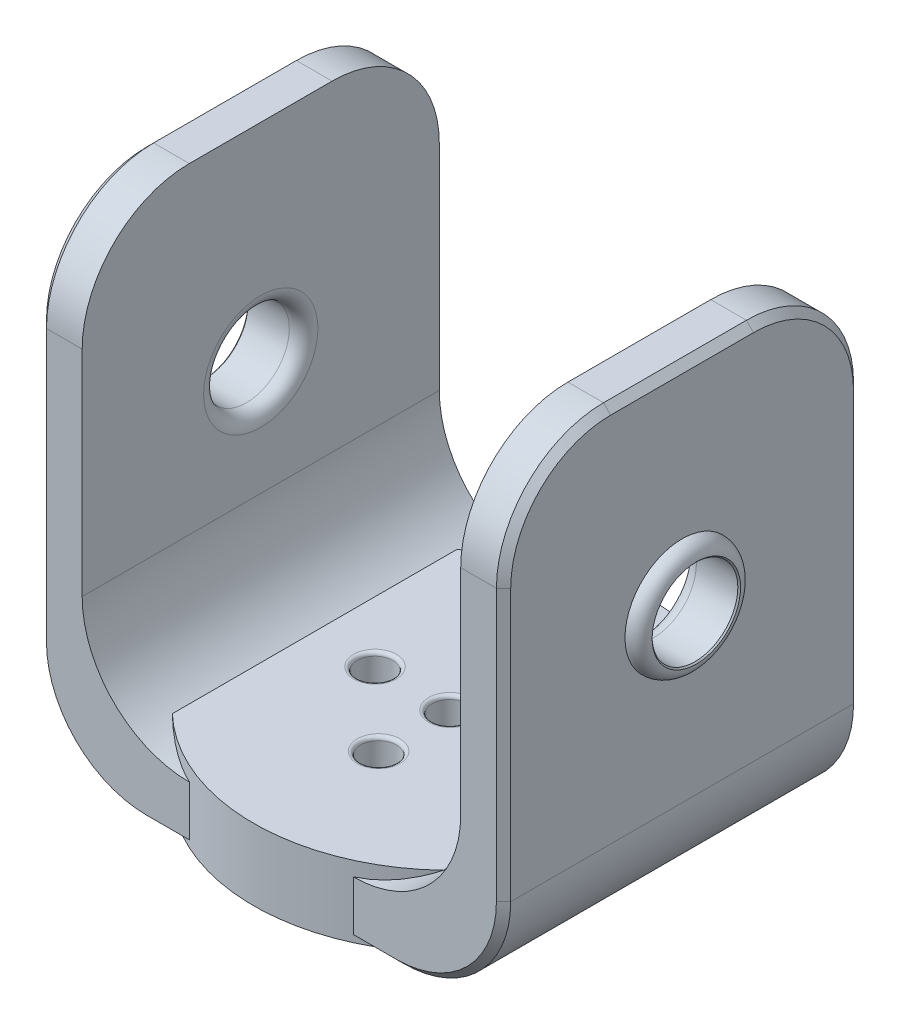
SolidWorks part; units mm, degrees
ref_plane "Front Plane" through (0, 0, 0) normal (0, 0, 1) x (1, 0, 0)
ref_plane "Top Plane" through (0, 0, 0) normal (0, 1, 0) x (1, 0, 0)
ref_plane "Right Plane" through (0, 0, 0) normal (1, 0, 0) x (0, 0, -1)
sketch "Sketch1" plane through (0, 0, 0) normal (0, 0, 1) x (1, 0, 0)
  line L0 (0, 0) -> (0, -68)
  line L1 (0, -68) -> (65, -68)
  line L2 (65, -68) -> (65, 0)
  line L3 (65, 0) -> (59, 0)
  line L4 (59, 0) -> (59, -60)
  line L5 (59, -60) -> (6, -60)
  line L6 (6, -60) -> (6, 0)
  line L7 (6, 0) -> (0, 0)
  dimension "D1" = 6
  dimension "D2" = 6
  dimension "D3" = 68
  dimension "D4" = 8
  dimension "D5" = 65
extrude "Boss-Extrude1" add sketch "Sketch1" along normal blind 50
sketch "Sketch2" plane through (0, -68, 0) normal (0, -1, 0) x (1, 0, 0)
  line L3 (0, 50) -> (0, 0) construction
  line L4 (0, 50) -> (65, 50) construction
  circle A0 centre (32.5, 25) radius 27.5
  point P10 (0, 25)
  point P13 (32.5, 50)
  dimension "D1" = 55
extrude "Boss-Extrude2" add sketch "Sketch2" against normal blind 10
fillet "Fillet1" radius 15 6 edges at (65, -68, 25) (59, -60, 41.1742) (59, -60, 8.8258) (0, -68, 25) (6, -60, 8.8258) (6, -60, 41.1742)
fillet "Fillet2" radius 15 4 edges at (62, 0, 50) (62, 0, 0) (3, 0, 50) (3, 0, 0)
sketch "Sketch3" plane through (65, 0, 0) normal (1, 0, 0) x (0, 0, -1)
  line L0 (-50, -58) -> (-52.5, -58) construction
  circle A0 centre (-25, -29) radius 6
  dimension "D1" = 12
  dimension "D2" = 29
extrude "Cut-Extrude1" cut sketch "Sketch3" against normal blind 90
sketch "Sketch4" plane through (65, 0, 0) normal (1, 0, 0) x (0, 0, -1)
  circle A0 centre (-25, -29) radius 8
  circle M1 centre (-25, -29) radius 6
  dimension "D1" = 16
extrude "Boss-Extrude7" add sketch "Sketch4" along normal blind 2 contours A0 M1 region at (65, -29, 32.7737)
fillet "Fillet3" radius 2 1 edges at (67, -29, 17)
fillet "Fillet20" radius 2 1 edges at (59, -23, 25)
sketch "Sketch9" plane through (0, 0, 0) normal (-1, 0, 0) x (0, 0, 1)
  circle A0 centre (25, -29) radius 8
  circle M1 centre (25, -29) radius 6
  dimension "D1" = 16
extrude "Boss-Extrude11" add sketch "Sketch9" along normal blind 2 contours A0 M1 region at (0, -29, 17.2263)
fillet "Fillet24" radius 2 1 edges at (-2, -37, 25)
fillet "Fillet25" radius 2 1 edges at (6, -29, 31)
chamfer "Chamfer12" distance 1 9 edges at (0, -4.3934, 45.6066) (18.0218, -68, 50) (4.3934, -63.6066, 50) (0, -34, 50) (18.0218, -68, 0) (4.3934, -63.6066, 0) (0, 0, 25) (0, -34, 0) (0, -4.3934, 4.3934)
chamfer "Chamfer13" distance 1 9 edges at (65, -4.3934, 45.6066) (46.9782, -68, 50) (60.6066, -63.6066, 50) (46.9782, -68, 0) (65, -34, 50) (60.6066, -63.6066, 0) (65, -34, 0) (65, 0, 25) (65, -4.3934, 4.3934)
chamfer "Chamfer16" distance 0.2 angle 45 1 edges at (-2, -35, 25)
chamfer "Chamfer17" distance 0.2 angle 45 1 edges at (67, -29, 19)
sketch "Sketch10" plane through (0, -68, 0) normal (0, -1, 0) x (1, 0, 0)
  circle A0 centre (32.5, 25) radius 2.5
  circle A1 centre (32.5, 35) radius 2.5
  circle A2 centre (42.5, 25) radius 2.5
  circle A3 centre (32.5, 15) radius 2.5
  circle A4 centre (22.0017, 25) radius 2.5
  dimension "D4" = 5
  dimension "D1" = 10
  dimension "D2" = 10
  dimension "D3" = 10
extrude "Cut-Extrude2" cut sketch "Sketch10" against normal blind 10
fillet "Fillet27" radius 0.5 5 edges at (42.5, -58, 22.5) (32.5, -58, 32.5) (32.5, -58, 22.5) (32.5, -58, 12.5) (22.0017, -58, 22.5)
chamfer "Chamfer18" distance 0.5 angle 45 5 edges at (42.5, -68, 22.5) (32.5, -68, 32.5) (32.5, -68, 22.5) (32.5, -68, 12.5) (22.0017, -68, 22.5)
sketch "Sketch21" plane through (0, 0, 0) normal (1, 0, 0) x (0, 0, -1)
  line L1153 (-7.1413, -11.9492) -> (-7.1388, -11.9501)
  line L1154 (-7.1504, -11.9458) -> (-7.1413, -11.9492)
  line L1155 (-7.1569, -11.9436) -> (-7.1504, -11.9458)
  line L1156 (-7.1581, -11.9434) -> (-7.1569, -11.9436)
  line L1157 (-7.1589, -11.9433) -> (-7.1581, -11.9434)
  line L1158 (-7.1635, -11.9443) -> (-7.1589, -11.9433)
  line L1159 (-7.1705, -11.9468) -> (-7.1635, -11.9443)
  line L1160 (-7.1724, -11.9473) -> (-7.1705, -11.9468)
  line L1161 (-7.1678, -11.9518) -> (-7.1724, -11.9473)
  line L1162 (-7.1557, -11.9674) -> (-7.1678, -11.9518)
  line L1163 (-7.1418, -11.9889) -> (-7.1557, -11.9674)
  line L1164 (-7.1272, -12.0098) -> (-7.1418, -11.9889)
  line L1165 (-7.1135, -12.0243) -> (-7.1272, -12.0098)
  line L1166 (-7.1083, -12.0283) -> (-7.1135, -12.0243)
  line L1167 (-7.1038, -12.0239) -> (-7.1083, -12.0283)
  line L1168 (-7.0833, -12.0007) -> (-7.1038, -12.0239)
  line L1169 (-7.0674, -11.9728) -> (-7.0833, -12.0007)
  line L1170 (-7.0651, -11.9662) -> (-7.0674, -11.9728)
  line L1171 (-7.0716, -11.9647) -> (-7.0651, -11.9662)
  line L1172 (-7.1329, -11.9513) -> (-7.0716, -11.9647)
  line L1173 (-7.1388, -11.9501) -> (-7.1329, -11.9513)
  line L1174 (-5.1665, -14.3943) -> (-5.1595, -14.401)
  line L1175 (-5.1997, -14.3633) -> (-5.1665, -14.3943)
  line L1176 (-5.231, -14.3342) -> (-5.1997, -14.3633)
  line L1177 (-5.2371, -14.3285) -> (-5.231, -14.3342)
  line L1178 (-5.2189, -14.3642) -> (-5.2371, -14.3285)
  line L1179 (-5.1593, -14.4686) -> (-5.2189, -14.3642)
  line L1180 (-5.0702, -14.6006) -> (-5.1593, -14.4686)
  line L1181 (-4.9674, -14.7233) -> (-5.0702, -14.6006)
  line L1182 (-4.8797, -14.8095) -> (-4.9674, -14.7233)
  line L1183 (-4.8484, -14.8356) -> (-4.8797, -14.8095)
  line L1184 (-4.8609, -14.8037) -> (-4.8484, -14.8356)
  line L1185 (-4.9079, -14.7116) -> (-4.8609, -14.8037)
  line L1186 (-4.9814, -14.5996) -> (-4.9079, -14.7116)
  line L1187 (-5.0662, -14.497) -> (-4.9814, -14.5996)
  line L1188 (-5.1355, -14.4243) -> (-5.0662, -14.497)
  line L1189 (-5.1595, -14.401) -> (-5.1355, -14.4243)
  line L1190 (-6.2442, -12.7333) -> (-6.2379, -12.7676)
  line L1191 (-6.266, -12.6309) -> (-6.2442, -12.7333)
  line L1192 (-6.3012, -12.4978) -> (-6.266, -12.6309)
  line L1193 (-6.3468, -12.3691) -> (-6.3012, -12.4978)
  line L1194 (-6.3895, -12.2751) -> (-6.3468, -12.3691)
  line L1195 (-6.4062, -12.2452) -> (-6.3895, -12.2751)
  line L1196 (-6.4101, -12.238) -> (-6.4062, -12.2452)
  line L1197 (-6.4242, -12.2177) -> (-6.4101, -12.238)
  line L1198 (-6.4431, -12.2024) -> (-6.4242, -12.2177)
  line L1199 (-6.467, -12.1978) -> (-6.4431, -12.2024)
  line L1200 (-6.492, -12.2005) -> (-6.467, -12.1978)
  line L1201 (-6.5001, -12.2024) -> (-6.492, -12.2005)
  line L1202 (-6.5135, -12.2054) -> (-6.5001, -12.2024)
  line L1203 (-6.5525, -12.2206) -> (-6.5135, -12.2054)
  line L1204 (-6.5982, -12.2485) -> (-6.5525, -12.2206)
  line L1205 (-6.6386, -12.2839) -> (-6.5982, -12.2485)
  line L1206 (-6.6665, -12.3139) -> (-6.6386, -12.2839)
  line L1207 (-6.6752, -12.3244) -> (-6.6665, -12.3139)
  line L1208 (-6.6804, -12.3306) -> (-6.6752, -12.3244)
  line L1209 (-6.6959, -12.3497) -> (-6.6804, -12.3306)
  line L1210 (-6.7105, -12.3696) -> (-6.6959, -12.3497)
  line L1211 (-6.7188, -12.3855) -> (-6.7105, -12.3696)
  line L1212 (-6.7206, -12.3992) -> (-6.7188, -12.3855)
  line L1213 (-6.7158, -12.4123) -> (-6.7206, -12.3992)
  line L1214 (-6.7042, -12.4262) -> (-6.7158, -12.4123)
  line L1215 (-6.6858, -12.4428) -> (-6.7042, -12.4262)
  line L1216 (-6.6668, -12.4584) -> (-6.6858, -12.4428)
  line L1217 (-6.6604, -12.4635) -> (-6.6668, -12.4584)
  line L1218 (-6.6282, -12.4893) -> (-6.6604, -12.4635)
  line L1219 (-6.2993, -12.7384) -> (-6.6282, -12.4893)
  line L1220 (-6.2659, -12.7626) -> (-6.2993, -12.7384)
  line L1221 (-6.2645, -12.7637) -> (-6.2659, -12.7626)
  line L1222 (-6.2608, -12.7678) -> (-6.2645, -12.7637)
  line L1223 (-6.2544, -12.7738) -> (-6.2608, -12.7678)
  line L1224 (-6.2467, -12.7754) -> (-6.2544, -12.7738)
  line L1225 (-6.2394, -12.7699) -> (-6.2467, -12.7754)
  line L1226 (-6.2379, -12.7676) -> (-6.2394, -12.7699)
  line L1227 (-6.7383, -12.3211) -> (-6.7449, -12.3295)
  line L1228 (-6.7182, -12.2959) -> (-6.7383, -12.3211)
  line L1229 (-6.6948, -12.2688) -> (-6.7182, -12.2959)
  line L1230 (-6.6723, -12.2464) -> (-6.6948, -12.2688)
  line L1231 (-6.6482, -12.2268) -> (-6.6723, -12.2464)
  line L1232 (-6.6198, -12.2081) -> (-6.6482, -12.2268)
  line L1233 (-6.5847, -12.1885) -> (-6.6198, -12.2081)
  line L1234 (-6.5403, -12.1662) -> (-6.5847, -12.1885)
  line L1235 (-6.4981, -12.146) -> (-6.5403, -12.1662)
  line L1236 (-6.484, -12.1394) -> (-6.4981, -12.146)
  line L1237 (-6.4865, -12.1328) -> (-6.484, -12.1394)
  line L1238 (-6.4974, -12.1143) -> (-6.4865, -12.1328)
  line L1239 (-6.5152, -12.0931) -> (-6.4974, -12.1143)
  line L1240 (-6.5354, -12.0741) -> (-6.5152, -12.0931)
  line L1241 (-6.5511, -12.0604) -> (-6.5354, -12.0741)
  line L1242 (-6.5562, -12.0557) -> (-6.5511, -12.0604)
  line L1243 (-6.5707, -12.0425) -> (-6.5562, -12.0557)
  line L1244 (-6.6171, -12.006) -> (-6.5707, -12.0425)
  line L1245 (-6.6827, -11.9661) -> (-6.6171, -12.006)
  line L1246 (-6.754, -11.9385) -> (-6.6827, -11.9661)
  line L1247 (-6.8126, -11.9268) -> (-6.754, -11.9385)
  line L1248 (-6.8322, -11.9258) -> (-6.8126, -11.9268)
  line L1249 (-6.8495, -11.9248) -> (-6.8322, -11.9258)
  line L1250 (-6.9019, -11.9302) -> (-6.8495, -11.9248)
  line L1251 (-6.9623, -11.9519) -> (-6.9019, -11.9302)
  line L1252 (-7.0131, -11.9912) -> (-6.9623, -11.9519)
  line L1253 (-7.0459, -12.0332) -> (-7.0131, -11.9912)
  line L1254 (-7.0543, -12.0485) -> (-7.0459, -12.0332)
  line L1255 (-7.0565, -12.0527) -> (-7.0543, -12.0485)
  line L1256 (-7.0605, -12.0666) -> (-7.0565, -12.0527)
  line L1257 (-7.0589, -12.0819) -> (-7.0605, -12.0666)
  line L1258 (-7.0514, -12.0954) -> (-7.0589, -12.0819)
  line L1259 (-7.0432, -12.105) -> (-7.0514, -12.0954)
  line L1260 (-7.0402, -12.108) -> (-7.0432, -12.105)
  line L1261 (-7.0229, -12.1252) -> (-7.0402, -12.108)
  line L1262 (-6.8497, -12.2969) -> (-7.0229, -12.1252)
  line L1263 (-6.8324, -12.314) -> (-6.8497, -12.2969)
  line L1264 (-6.8302, -12.3161) -> (-6.8324, -12.314)
  line L1265 (-6.8061, -12.336) -> (-6.8302, -12.3161)
  line L1266 (-6.8041, -12.3383) -> (-6.8061, -12.336)
  line L1267 (-6.8002, -12.3425) -> (-6.8041, -12.3383)
  line L1268 (-6.7865, -12.3531) -> (-6.8002, -12.3425)
  line L1269 (-6.7709, -12.3564) -> (-6.7865, -12.3531)
  line L1270 (-6.7571, -12.3485) -> (-6.7709, -12.3564)
  line L1271 (-6.7473, -12.3346) -> (-6.7571, -12.3485)
  line L1272 (-6.7449, -12.3295) -> (-6.7473, -12.3346)
  line L1273 (-7.708, -13.2169) -> (-7.692, -13.1989)
  line L1274 (-7.763, -13.2649) -> (-7.708, -13.2169)
  line L1275 (-7.842, -13.3122) -> (-7.763, -13.2649)
  line L1276 (-7.9297, -13.3416) -> (-7.842, -13.3122)
  line L1277 (-8.0025, -13.353) -> (-7.9297, -13.3416)
  line L1278 (-8.0269, -13.3541) -> (-8.0025, -13.353)
  line L1279 (-8.017, -13.3654) -> (-8.0269, -13.3541)
  line L1280 (-7.9696, -13.4201) -> (-8.017, -13.3654)
  line L1281 (-7.9229, -13.4722) -> (-7.9696, -13.4201)
  line L1282 (-7.9133, -13.4822) -> (-7.9229, -13.4722)
  line L1283 (-7.8971, -13.4989) -> (-7.9133, -13.4822)
  line L1284 (-7.8111, -13.5758) -> (-7.8971, -13.4989)
  line L1285 (-7.7171, -13.6432) -> (-7.8111, -13.5758)
  line L1286 (-7.6971, -13.6552) -> (-7.7171, -13.6432)
  line L1287 (-7.6737, -13.6692) -> (-7.6971, -13.6552)
  line L1288 (-7.5948, -13.6965) -> (-7.6737, -13.6692)
  line L1289 (-7.5007, -13.6959) -> (-7.5948, -13.6965)
  line L1290 (-7.4131, -13.6573) -> (-7.5007, -13.6959)
  line L1291 (-7.3487, -13.605) -> (-7.4131, -13.6573)
  line L1292 (-7.3302, -13.585) -> (-7.3487, -13.605)
  line L1293 (-7.3079, -13.5608) -> (-7.3302, -13.585)
  line L1294 (-7.2502, -13.4798) -> (-7.3079, -13.5608)
  line L1295 (-7.1903, -13.3653) -> (-7.2502, -13.4798)
  line L1296 (-7.1445, -13.2443) -> (-7.1903, -13.3653)
  line L1297 (-7.1159, -13.1506) -> (-7.1445, -13.2443)
  line L1298 (-7.1071, -13.1193) -> (-7.1159, -13.1506)
  line L1299 (-7.1061, -13.1159) -> (-7.1071, -13.1193)
  line L1300 (-7.1053, -13.0996) -> (-7.1061, -13.1159)
  line L1301 (-7.1139, -13.0853) -> (-7.1053, -13.0996)
  line L1302 (-7.1177, -13.0828) -> (-7.1139, -13.0853)
  line L1303 (-7.1462, -13.0642) -> (-7.1177, -13.0828)
  line L1304 (-7.284, -12.9637) -> (-7.1462, -13.0642)
  line L1305 (-7.4244, -12.867) -> (-7.284, -12.9637)
  line L1306 (-7.4542, -12.8503) -> (-7.4244, -12.867)
  line L1307 (-7.4552, -12.8497) -> (-7.4542, -12.8503)
  line L1308 (-7.4679, -12.8448) -> (-7.4552, -12.8497)
  line L1309 (-7.4696, -12.8442) -> (-7.4679, -12.8448)
  line L1310 (-7.4812, -12.8679) -> (-7.4696, -12.8442)
  line L1311 (-7.5162, -12.9391) -> (-7.4812, -12.8679)
  line L1312 (-7.5656, -13.0317) -> (-7.5162, -12.9391)
  line L1313 (-7.6226, -13.1193) -> (-7.5656, -13.0317)
  line L1314 (-7.6731, -13.1806) -> (-7.6226, -13.1193)
  line L1315 (-7.692, -13.1989) -> (-7.6731, -13.1806)
  line L1316 (-6.3299, -12.2765) -> (-6.3467, -12.2436)
  line L1317 (-6.2867, -12.3792) -> (-6.3299, -12.2765)
  line L1318 (-6.2413, -12.5176) -> (-6.2867, -12.3792)
  line L1319 (-6.2068, -12.6582) -> (-6.2413, -12.5176)
  line L1320 (-6.1858, -12.7647) -> (-6.2068, -12.6582)
  line L1321 (-6.1797, -12.8004) -> (-6.1858, -12.7647)
  line L1322 (-6.1783, -12.8082) -> (-6.1797, -12.8004)
  line L1323 (-6.1684, -12.8306) -> (-6.1783, -12.8082)
  line L1324 (-6.1494, -12.8527) -> (-6.1684, -12.8306)
  line L1325 (-6.1261, -12.87) -> (-6.1494, -12.8527)
  line L1326 (-6.1081, -12.8817) -> (-6.1261, -12.87)
  line L1327 (-6.1023, -12.8859) -> (-6.1081, -12.8817)
  line L1328 (-6.062, -12.9146) -> (-6.1023, -12.8859)
  line L1329 (-5.6661, -13.2103) -> (-6.062, -12.9146)
  line L1330 (-5.6271, -13.2408) -> (-5.6661, -13.2103)
  line L1331 (-5.6267, -13.2411) -> (-5.6271, -13.2408)
  line L1332 (-5.6191, -13.2436) -> (-5.6267, -13.2411)
  line L1333 (-5.618, -13.244) -> (-5.6191, -13.2436)
  line L1334 (-5.6166, -13.2372) -> (-5.618, -13.244)
  line L1335 (-5.6191, -13.2049) -> (-5.6166, -13.2372)
  line L1336 (-5.6265, -13.1737) -> (-5.6191, -13.2049)
  line L1337 (-5.6277, -13.1675) -> (-5.6265, -13.1737)
  line L1338 (-5.6377, -13.1122) -> (-5.6277, -13.1675)
  line L1339 (-5.6924, -12.8364) -> (-5.6377, -13.1122)
  line L1340 (-5.7574, -12.5629) -> (-5.6924, -12.8364)
  line L1341 (-5.7726, -12.5087) -> (-5.7574, -12.5629)
  line L1342 (-5.7827, -12.4725) -> (-5.7726, -12.5087)
  line L1343 (-5.8164, -12.3648) -> (-5.7827, -12.4725)
  line L1344 (-5.8684, -12.2244) -> (-5.8164, -12.3648)
  line L1345 (-5.9313, -12.0884) -> (-5.8684, -12.2244)
  line L1346 (-5.9869, -11.9897) -> (-5.9313, -12.0884)
  line L1347 (-6.0076, -11.9583) -> (-5.9869, -11.9897)
  line L1348 (-6.0191, -11.9409) -> (-6.0076, -11.9583)
  line L1349 (-6.0816, -11.8586) -> (-6.0191, -11.9409)
  line L1350 (-6.153, -11.7841) -> (-6.0816, -11.8586)
  line L1351 (-6.1688, -11.7707) -> (-6.153, -11.7841)
  line L1352 (-6.1835, -11.7583) -> (-6.1688, -11.7707)
  line L1353 (-6.2332, -11.7278) -> (-6.1835, -11.7583)
  line L1354 (-6.3025, -11.702) -> (-6.2332, -11.7278)
  line L1355 (-6.3763, -11.6906) -> (-6.3025, -11.702)
  line L1356 (-6.4344, -11.6899) -> (-6.3763, -11.6906)
  line L1357 (-6.4537, -11.6913) -> (-6.4344, -11.6899)
  line L1358 (-6.4836, -11.6935) -> (-6.4537, -11.6913)
  line L1359 (-6.5728, -11.7096) -> (-6.4836, -11.6935)
  line L1360 (-6.6851, -11.7449) -> (-6.5728, -11.7096)
  line L1361 (-6.7914, -11.7957) -> (-6.6851, -11.7449)
  line L1362 (-6.8682, -11.8427) -> (-6.7914, -11.7957)
  line L1363 (-6.8926, -11.8601) -> (-6.8682, -11.8427)
  line L1364 (-6.8933, -11.8607) -> (-6.8926, -11.8601)
  line L1365 (-6.9003, -11.867) -> (-6.8933, -11.8607)
  line L1366 (-6.9009, -11.8677) -> (-6.9003, -11.867)
  line L1367 (-6.9013, -11.8681) -> (-6.9009, -11.8677)
  line L1368 (-6.9046, -11.8748) -> (-6.9013, -11.8681)
  line L1369 (-6.9051, -11.8758) -> (-6.9046, -11.8748)
  line L1370 (-6.8782, -11.8732) -> (-6.9051, -11.8758)
  line L1371 (-6.7964, -11.8781) -> (-6.8782, -11.8732)
  line L1372 (-6.6973, -11.9048) -> (-6.7964, -11.8781)
  line L1373 (-6.6063, -11.953) -> (-6.6973, -11.9048)
  line L1374 (-6.5415, -12.0018) -> (-6.6063, -11.953)
  line L1375 (-6.5218, -12.02) -> (-6.5415, -12.0018)
  line L1376 (-6.504, -12.0364) -> (-6.5218, -12.02)
  line L1377 (-6.4258, -12.1255) -> (-6.504, -12.0364)
  line L1378 (-6.3588, -12.223) -> (-6.4258, -12.1255)
  line L1379 (-6.3467, -12.2436) -> (-6.3588, -12.223)
  line L1380 (-4.9031, -15.3696) -> (-4.9159, -15.3718)
  line L1381 (-4.8661, -15.3557) -> (-4.9031, -15.3696)
  line L1382 (-4.8301, -15.3282) -> (-4.8661, -15.3557)
  line L1383 (-4.8053, -15.2913) -> (-4.8301, -15.3282)
  line L1384 (-4.7923, -15.2583) -> (-4.8053, -15.2913)
  line L1385 (-4.7894, -15.247) -> (-4.7923, -15.2583)
  line L1386 (-4.7826, -15.2212) -> (-4.7894, -15.247)
  line L1387 (-4.7795, -15.0944) -> (-4.7826, -15.2212)
  line L1388 (-4.8039, -14.9693) -> (-4.7795, -15.0944)
  line L1389 (-4.811, -14.9445) -> (-4.8039, -14.9693)
  line L1390 (-4.8122, -14.9401) -> (-4.811, -14.9445)
  line L1391 (-4.8235, -14.922) -> (-4.8122, -14.9401)
  line L1392 (-4.8395, -14.9071) -> (-4.8235, -14.922)
  line L1393 (-4.8431, -14.9043) -> (-4.8395, -14.9071)
  line L1394 (-4.8627, -14.8891) -> (-4.8431, -14.9043)
  line L1395 (-4.9566, -14.8088) -> (-4.8627, -14.8891)
  line L1396 (-5.0431, -14.7205) -> (-4.9566, -14.8088)
  line L1397 (-5.0589, -14.7013) -> (-5.0431, -14.7205)
  line L1398 (-5.0846, -14.67) -> (-5.0589, -14.7013)
  line L1399 (-5.2003, -14.5047) -> (-5.0846, -14.67)
  line L1400 (-5.2993, -14.3293) -> (-5.2003, -14.5047)
  line L1401 (-5.3168, -14.2928) -> (-5.2993, -14.3293)
  line L1402 (-5.3223, -14.2813) -> (-5.3168, -14.2928)
  line L1403 (-5.3446, -14.2492) -> (-5.3223, -14.2813)
  line L1404 (-5.379, -14.2143) -> (-5.3446, -14.2492)
  line L1405 (-5.4174, -14.1843) -> (-5.379, -14.2143)
  line L1406 (-5.4472, -14.1631) -> (-5.4174, -14.1843)
  line L1407 (-5.457, -14.1559) -> (-5.4472, -14.1631)
  line L1408 (-5.4968, -14.1266) -> (-5.457, -14.1559)
  line L1409 (-5.6995, -13.9853) -> (-5.4968, -14.1266)
  line L1410 (-5.9054, -13.8487) -> (-5.6995, -13.9853)
  line L1411 (-5.9468, -13.8218) -> (-5.9054, -13.8487)
  line L1412 (-5.9473, -13.8215) -> (-5.9468, -13.8218)
  line L1413 (-5.9562, -13.8201) -> (-5.9473, -13.8215)
  line L1414 (-5.9577, -13.8198) -> (-5.9562, -13.8201)
  line L1415 (-5.951, -13.8435) -> (-5.9577, -13.8198)
  line L1416 (-5.8849, -14.0778) -> (-5.951, -13.8435)
  line L1417 (-5.8779, -14.101) -> (-5.8849, -14.0778)
  line L1418 (-5.8649, -14.1435) -> (-5.8779, -14.101)
  line L1419 (-5.7968, -14.3551) -> (-5.8649, -14.1435)
  line L1420 (-5.7185, -14.563) -> (-5.7968, -14.3551)
  line L1421 (-5.7005, -14.6037) -> (-5.7185, -14.563)
  line L1422 (-5.6837, -14.6415) -> (-5.7005, -14.6037)
  line L1423 (-5.5894, -14.8243) -> (-5.6837, -14.6415)
  line L1424 (-5.4778, -14.9976) -> (-5.5894, -14.8243)
  line L1425 (-5.4524, -15.0306) -> (-5.4778, -14.9976)
  line L1426 (-5.4319, -15.0574) -> (-5.4524, -15.0306)
  line L1427 (-5.3188, -15.1781) -> (-5.4319, -15.0574)
  line L1428 (-5.1894, -15.2799) -> (-5.3188, -15.1781)
  line L1429 (-5.1606, -15.2971) -> (-5.1894, -15.2799)
  line L1430 (-5.1419, -15.3083) -> (-5.1606, -15.2971)
  line L1431 (-5.0435, -15.3512) -> (-5.1419, -15.3083)
  line L1432 (-4.9381, -15.3717) -> (-5.0435, -15.3512)
  line L1433 (-4.9159, -15.3718) -> (-4.9381, -15.3717)
  line L1434 (-5.3746, -11.4587) -> (-5.3621, -11.4847)
  line L1435 (-5.4332, -11.3297) -> (-5.3746, -11.4587)
  line L1436 (-5.4961, -11.2033) -> (-5.4332, -11.3297)
  line L1437 (-5.5108, -11.1785) -> (-5.4961, -11.2033)
  line L1438 (-5.513, -11.1891) -> (-5.5108, -11.1785)
  line L1439 (-5.5204, -11.2206) -> (-5.513, -11.1891)
  line L1440 (-5.5326, -11.2604) -> (-5.5204, -11.2206)
  line L1441 (-5.5489, -11.2978) -> (-5.5326, -11.2604)
  line L1442 (-5.5649, -11.3243) -> (-5.5489, -11.2978)
  line L1443 (-5.5711, -11.3324) -> (-5.5649, -11.3243)
  line L1444 (-5.5797, -11.3434) -> (-5.5711, -11.3324)
  line L1445 (-5.6113, -11.3719) -> (-5.5797, -11.3434)
  line L1446 (-5.6579, -11.3977) -> (-5.6113, -11.3719)
  line L1447 (-5.709, -11.4127) -> (-5.6579, -11.3977)
  line L1448 (-5.7495, -11.4188) -> (-5.709, -11.4127)
  line L1449 (-5.763, -11.4197) -> (-5.7495, -11.4188)
  line L1450 (-5.7961, -11.422) -> (-5.763, -11.4197)
  line L1451 (-5.9616, -11.4305) -> (-5.7961, -11.422)
  line L1452 (-6.1271, -11.4276) -> (-5.9616, -11.4305)
  line L1453 (-6.1602, -11.4243) -> (-6.1271, -11.4276)
  line L1454 (-6.1859, -11.4216) -> (-6.1602, -11.4243)
  line L1455 (-6.4419, -11.3819) -> (-6.1859, -11.4216)
  line L1456 (-6.4675, -11.3781) -> (-6.4419, -11.3819)
  line L1457 (-6.4996, -11.3734) -> (-6.4675, -11.3781)
  line L1458 (-6.6585, -11.3387) -> (-6.4996, -11.3734)
  line L1459 (-6.8186, -11.3132) -> (-6.6585, -11.3387)
  line L1460 (-6.8514, -11.3129) -> (-6.8186, -11.3132)
  line L1461 (-6.8758, -11.3127) -> (-6.8514, -11.3129)
  line L1462 (-6.9967, -11.3221) -> (-6.8758, -11.3127)
  line L1463 (-7.1148, -11.3514) -> (-6.9967, -11.3221)
  line L1464 (-7.1378, -11.3611) -> (-7.1148, -11.3514)
  line L1465 (-7.1557, -11.3687) -> (-7.1378, -11.3611)
  line L1466 (-7.2047, -11.4022) -> (-7.1557, -11.3687)
  line L1467 (-7.2556, -11.4616) -> (-7.2047, -11.4022)
  line L1468 (-7.2863, -11.5372) -> (-7.2556, -11.4616)
  line L1469 (-7.2941, -11.6046) -> (-7.2863, -11.5372)
  line L1470 (-7.2923, -11.6267) -> (-7.2941, -11.6046)
  line L1471 (-7.2907, -11.6464) -> (-7.2923, -11.6267)
  line L1472 (-7.274, -11.7414) -> (-7.2907, -11.6464)
  line L1473 (-7.2421, -11.8318) -> (-7.274, -11.7414)
  line L1474 (-7.2329, -11.8493) -> (-7.2421, -11.8318)
  line L1475 (-7.2312, -11.8525) -> (-7.2329, -11.8493)
  line L1476 (-7.2215, -11.8667) -> (-7.2312, -11.8525)
  line L1477 (-7.2082, -11.8765) -> (-7.2215, -11.8667)
  line L1478 (-7.2046, -11.8775) -> (-7.2082, -11.8765)
  line L1479 (-7.1908, -11.8814) -> (-7.2046, -11.8775)
  line L1480 (-7.1217, -11.9008) -> (-7.1908, -11.8814)
  line L1481 (-7.0515, -11.9154) -> (-7.1217, -11.9008)
  line L1482 (-7.0371, -11.9169) -> (-7.0515, -11.9154)
  line L1483 (-7.0328, -11.9174) -> (-7.0371, -11.9169)
  line L1484 (-7.017, -11.9113) -> (-7.0328, -11.9174)
  line L1485 (-7.0053, -11.8997) -> (-7.017, -11.9113)
  line L1486 (-7.0031, -11.8974) -> (-7.0053, -11.8997)
  line L1487 (-6.9765, -11.8694) -> (-7.0031, -11.8974)
  line L1488 (-6.8864, -11.795) -> (-6.9765, -11.8694)
  line L1489 (-6.7572, -11.7192) -> (-6.8864, -11.795)
  line L1490 (-6.616, -11.6683) -> (-6.7572, -11.7192)
  line L1491 (-6.5017, -11.6448) -> (-6.616, -11.6683)
  line L1492 (-6.4632, -11.6409) -> (-6.5017, -11.6448)
  line L1493 (-6.4301, -11.6375) -> (-6.4632, -11.6409)
  line L1494 (-6.3292, -11.6448) -> (-6.4301, -11.6375)
  line L1495 (-6.2129, -11.6837) -> (-6.3292, -11.6448)
  line L1496 (-6.1116, -11.7537) -> (-6.2129, -11.6837)
  line L1497 (-6.0423, -11.8253) -> (-6.1116, -11.7537)
  line L1498 (-6.0223, -11.8515) -> (-6.0423, -11.8253)
  line L1499 (-6.0006, -11.8798) -> (-6.0223, -11.8515)
  line L1500 (-5.9061, -12.0288) -> (-6.0006, -11.8798)
  line L1501 (-5.8281, -12.1867) -> (-5.9061, -12.0288)
  line L1502 (-5.8148, -12.2196) -> (-5.8281, -12.1867)
  line L1503 (-5.8114, -12.228) -> (-5.8148, -12.2196)
  line L1504 (-5.78, -12.3131) -> (-5.8114, -12.228)
  line L1505 (-5.7771, -12.3217) -> (-5.78, -12.3131)
  line L1506 (-5.7756, -12.3265) -> (-5.7771, -12.3217)
  line L1507 (-5.7639, -12.3444) -> (-5.7756, -12.3265)
  line L1508 (-5.7455, -12.3538) -> (-5.7639, -12.3444)
  line L1509 (-5.7406, -12.3543) -> (-5.7455, -12.3538)
  line L1510 (-5.716, -12.3566) -> (-5.7406, -12.3543)
  line L1511 (-5.6418, -12.3605) -> (-5.716, -12.3566)
  line L1512 (-5.544, -12.3581) -> (-5.6418, -12.3605)
  line L1513 (-5.4476, -12.3434) -> (-5.544, -12.3581)
  line L1514 (-5.3757, -12.3223) -> (-5.4476, -12.3434)
  line L1515 (-5.353, -12.3125) -> (-5.3757, -12.3223)
  line L1516 (-5.3376, -12.3059) -> (-5.353, -12.3125)
  line L1517 (-5.2945, -12.2786) -> (-5.3376, -12.3059)
  line L1518 (-5.251, -12.2337) -> (-5.2945, -12.2786)
  line L1519 (-5.2227, -12.1776) -> (-5.251, -12.2337)
  line L1520 (-5.211, -12.1272) -> (-5.2227, -12.1776)
  line L1521 (-5.2098, -12.1102) -> (-5.211, -12.1272)
  line L1522 (-5.2079, -12.0853) -> (-5.2098, -12.1102)
  line L1523 (-5.2102, -12.01) -> (-5.2079, -12.0853)
  line L1524 (-5.2239, -11.9121) -> (-5.2102, -12.01)
  line L1525 (-5.2466, -11.8158) -> (-5.2239, -11.9121)
  line L1526 (-5.2671, -11.7441) -> (-5.2466, -11.8158)
  line L1527 (-5.2743, -11.7204) -> (-5.2671, -11.7441)
  line L1528 (-5.2803, -11.7003) -> (-5.2743, -11.7204)
  line L1529 (-5.3539, -11.504) -> (-5.2803, -11.7003)
  line L1530 (-5.3621, -11.4847) -> (-5.3539, -11.504)
  line L1531 (-9.0055, -11.6592) -> (-8.9922, -11.6748)
  line L1532 (-9.0465, -11.6135) -> (-9.0055, -11.6592)
  line L1533 (-9.1035, -11.5577) -> (-9.0465, -11.6135)
  line L1534 (-9.1659, -11.51) -> (-9.1035, -11.5577)
  line L1535 (-9.2184, -11.4806) -> (-9.1659, -11.51)
  line L1536 (-9.2369, -11.4733) -> (-9.2184, -11.4806)
  line L1537 (-9.2563, -11.4656) -> (-9.2369, -11.4733)
  line L1538 (-9.3528, -11.4536) -> (-9.2563, -11.4656)
  line L1539 (-9.4487, -11.4689) -> (-9.3528, -11.4536)
  line L1540 (-9.4678, -11.4748) -> (-9.4487, -11.4689)
  line L1541 (-9.4966, -11.4836) -> (-9.4678, -11.4748)
  line L1542 (-9.6295, -11.5488) -> (-9.4966, -11.4836)
  line L1543 (-9.7521, -11.6322) -> (-9.6295, -11.5488)
  line L1544 (-9.7759, -11.6502) -> (-9.7521, -11.6322)
  line L1545 (-9.7766, -11.6506) -> (-9.7759, -11.6502)
  line L1546 (-9.782, -11.6606) -> (-9.7766, -11.6506)
  line L1547 (-9.7828, -11.662) -> (-9.782, -11.6606)
  line L1548 (-9.7733, -11.6652) -> (-9.7828, -11.662)
  line L1549 (-9.7252, -11.6711) -> (-9.7733, -11.6652)
  line L1550 (-9.6777, -11.6773) -> (-9.7252, -11.6711)
  line L1551 (-9.6685, -11.6806) -> (-9.6777, -11.6773)
  line L1552 (-9.6501, -11.6872) -> (-9.6685, -11.6806)
  line L1553 (-9.5708, -11.7353) -> (-9.6501, -11.6872)
  line L1554 (-9.5051, -11.8008) -> (-9.5708, -11.7353)
  line L1555 (-9.4936, -11.816) -> (-9.5051, -11.8008)
  line L1556 (-9.47, -11.8473) -> (-9.4936, -11.816)
  line L1557 (-9.4111, -11.95) -> (-9.47, -11.8473)
  line L1558 (-9.3516, -12.0929) -> (-9.4111, -11.95)
  line L1559 (-9.3068, -12.2415) -> (-9.3516, -12.0929)
  line L1560 (-9.2778, -12.3547) -> (-9.3068, -12.2415)
  line L1561 (-9.2683, -12.3924) -> (-9.2778, -12.3547)
  line L1562 (-9.2536, -12.4502) -> (-9.2683, -12.3924)
  line L1563 (-9.168, -12.7349) -> (-9.2536, -12.4502)
  line L1564 (-9.0642, -13.0135) -> (-9.168, -12.7349)
  line L1565 (-9.0405, -13.0683) -> (-9.0642, -13.0135)
  line L1566 (-9.022, -13.1112) -> (-9.0405, -13.0683)
  line L1567 (-8.9176, -13.3193) -> (-9.022, -13.1112)
  line L1568 (-8.7971, -13.5182) -> (-8.9176, -13.3193)
  line L1569 (-8.7705, -13.5566) -> (-8.7971, -13.5182)
  line L1570 (-8.746, -13.5918) -> (-8.7705, -13.5566)
  line L1571 (-8.6113, -13.7578) -> (-8.746, -13.5918)
  line L1572 (-8.4574, -13.9067) -> (-8.6113, -13.7578)
  line L1573 (-8.4234, -13.9335) -> (-8.4574, -13.9067)
  line L1574 (-8.3945, -13.9562) -> (-8.4234, -13.9335)
  line L1575 (-8.3013, -14.0165) -> (-8.3945, -13.9562)
  line L1576 (-8.1716, -14.0776) -> (-8.3013, -14.0165)
  line L1577 (-8.0336, -14.1148) -> (-8.1716, -14.0776)
  line L1578 (-7.9231, -14.1264) -> (-8.0336, -14.1148)
  line L1579 (-7.8864, -14.1257) -> (-7.9231, -14.1264)
  line L1580 (-7.8578, -14.1252) -> (-7.8864, -14.1257)
  line L1581 (-7.7241, -14.095) -> (-7.8578, -14.1252)
  line L1582 (-7.6012, -14.0314) -> (-7.7241, -14.095)
  line L1583 (-7.5779, -14.0142) -> (-7.6012, -14.0314)
  line L1584 (-7.5511, -13.9943) -> (-7.5779, -14.0142)
  line L1585 (-7.4773, -13.9257) -> (-7.5511, -13.9943)
  line L1586 (-7.3938, -13.825) -> (-7.4773, -13.9257)
  line L1587 (-7.3241, -13.7142) -> (-7.3938, -13.825)
  line L1588 (-7.2787, -13.6256) -> (-7.3241, -13.7142)
  line L1589 (-7.2651, -13.5954) -> (-7.2787, -13.6256)
  line L1590 (-7.2647, -13.5945) -> (-7.2651, -13.5954)
  line L1591 (-7.262, -13.5844) -> (-7.2647, -13.5945)
  line L1592 (-7.2616, -13.583) -> (-7.262, -13.5844)
  line L1593 (-7.2719, -13.5945) -> (-7.2616, -13.583)
  line L1594 (-7.3241, -13.6492) -> (-7.2719, -13.5945)
  line L1595 (-7.3811, -13.6977) -> (-7.3241, -13.6492)
  line L1596 (-7.3939, -13.7061) -> (-7.3811, -13.6977)
  line L1597 (-7.4105, -13.7171) -> (-7.3939, -13.7061)
  line L1598 (-7.4662, -13.7413) -> (-7.4105, -13.7171)
  line L1599 (-7.539, -13.7535) -> (-7.4662, -13.7413)
  line L1600 (-7.6124, -13.7451) -> (-7.539, -13.7535)
  line L1601 (-7.6688, -13.7267) -> (-7.6124, -13.7451)
  line L1602 (-7.6866, -13.7183) -> (-7.6688, -13.7267)
  line L1603 (-7.7101, -13.7073) -> (-7.6866, -13.7183)
  line L1604 (-7.817, -13.637) -> (-7.7101, -13.7073)
  line L1605 (-7.9139, -13.5533) -> (-7.817, -13.637)
  line L1606 (-7.9324, -13.5355) -> (-7.9139, -13.5533)
  line L1607 (-7.9608, -13.5082) -> (-7.9324, -13.5355)
  line L1608 (-8.0889, -13.3607) -> (-7.9608, -13.5082)
  line L1609 (-8.2005, -13.2004) -> (-8.0889, -13.3607)
  line L1610 (-8.2207, -13.1666) -> (-8.2005, -13.2004)
  line L1611 (-8.2382, -13.1373) -> (-8.2207, -13.1666)
  line L1612 (-8.32, -12.9878) -> (-8.2382, -13.1373)
  line L1613 (-8.3963, -12.8354) -> (-8.32, -12.9878)
  line L1614 (-8.411, -12.8047) -> (-8.3963, -12.8354)
  line L1615 (-8.4419, -12.7403) -> (-8.411, -12.8047)
  line L1616 (-8.5875, -12.4143) -> (-8.4419, -12.7403)
  line L1617 (-8.7378, -12.0906) -> (-8.5875, -12.4143)
  line L1618 (-8.7711, -12.0273) -> (-8.7378, -12.0906)
  line L1619 (-8.7872, -11.9965) -> (-8.7711, -12.0273)
  line L1620 (-8.8739, -11.8461) -> (-8.7872, -11.9965)
  line L1621 (-8.9708, -11.7023) -> (-8.8739, -11.8461)
  line L1622 (-8.9922, -11.6748) -> (-8.9708, -11.7023)
  line L1623 (-4.949, -13.8706) -> (-4.9224, -13.895)
  line L1624 (-5.213, -13.6392) -> (-4.949, -13.8706)
  line L1625 (-5.2399, -13.6171) -> (-5.213, -13.6392)
  line L1626 (-5.2973, -13.5697) -> (-5.2399, -13.6171)
  line L1627 (-5.5871, -13.3359) -> (-5.2973, -13.5697)
  line L1628 (-5.8824, -13.1091) -> (-5.5871, -13.3359)
  line L1629 (-5.9427, -13.0652) -> (-5.8824, -13.1091)
  line L1630 (-5.99, -13.0308) -> (-5.9427, -13.0652)
  line L1631 (-6.4613, -12.6837) -> (-5.99, -13.0308)
  line L1632 (-6.508, -12.6484) -> (-6.4613, -12.6837)
  line L1633 (-6.5462, -12.6196) -> (-6.508, -12.6484)
  line L1634 (-6.7321, -12.4692) -> (-6.5462, -12.6196)
  line L1635 (-6.9106, -12.3097) -> (-6.7321, -12.4692)
  line L1636 (-6.9451, -12.2764) -> (-6.9106, -12.3097)
  line L1637 (-6.9735, -12.2488) -> (-6.9451, -12.2764)
  line L1638 (-7.1085, -12.105) -> (-6.9735, -12.2488)
  line L1639 (-7.2301, -11.9501) -> (-7.1085, -12.105)
  line L1640 (-7.2519, -11.9169) -> (-7.2301, -11.9501)
  line L1641 (-7.2638, -11.8988) -> (-7.2519, -11.9169)
  line L1642 (-7.2945, -11.8414) -> (-7.2638, -11.8988)
  line L1643 (-7.325, -11.762) -> (-7.2945, -11.8414)
  line L1644 (-7.3419, -11.6793) -> (-7.325, -11.762)
  line L1645 (-7.3453, -11.615) -> (-7.3419, -11.6793)
  line L1646 (-7.3439, -11.5938) -> (-7.3453, -11.615)
  line L1647 (-7.3421, -11.5677) -> (-7.3439, -11.5938)
  line L1648 (-7.3266, -11.4904) -> (-7.3421, -11.5677)
  line L1649 (-7.2849, -11.4064) -> (-7.3266, -11.4904)
  line L1650 (-7.2105, -11.3404) -> (-7.2849, -11.4064)
  line L1651 (-7.1251, -11.3001) -> (-7.2105, -11.3404)
  line L1652 (-7.0953, -11.2911) -> (-7.1251, -11.3001)
  line L1653 (-7.0881, -11.289) -> (-7.0953, -11.2911)
  line L1654 (-7.0525, -11.2781) -> (-7.0881, -11.289)
  line L1655 (-7.0157, -11.271) -> (-7.0525, -11.2781)
  line L1656 (-7.008, -11.2708) -> (-7.0157, -11.271)
  line L1657 (-7.038, -11.2635) -> (-7.008, -11.2708)
  line L1658 (-7.3399, -11.2123) -> (-7.038, -11.2635)
  line L1659 (-7.3702, -11.2082) -> (-7.3399, -11.2123)
  line L1660 (-7.4052, -11.2033) -> (-7.3702, -11.2082)
  line L1661 (-7.5799, -11.1905) -> (-7.4052, -11.2033)
  line L1662 (-7.7544, -11.1948) -> (-7.5799, -11.1905)
  line L1663 (-7.7893, -11.1986) -> (-7.7544, -11.1948)
  line L1664 (-7.8186, -11.2017) -> (-7.7893, -11.1986)
  line L1665 (-7.9057, -11.2196) -> (-7.8186, -11.2017)
  line L1666 (-8.0121, -11.2599) -> (-7.9057, -11.2196)
  line L1667 (-8.105, -11.3243) -> (-8.0121, -11.2599)
  line L1668 (-8.1657, -11.392) -> (-8.105, -11.3243)
  line L1669 (-8.1812, -11.4173) -> (-8.1657, -11.392)
  line L1670 (-8.1941, -11.4385) -> (-8.1812, -11.4173)
  line L1671 (-8.2446, -11.5501) -> (-8.1941, -11.4385)
  line L1672 (-8.2751, -11.6696) -> (-8.2446, -11.5501)
  line L1673 (-8.2779, -11.6948) -> (-8.2751, -11.6696)
  line L1674 (-8.281, -11.7218) -> (-8.2779, -11.6948)
  line L1675 (-8.2815, -11.8037) -> (-8.281, -11.7218)
  line L1676 (-8.2668, -11.9079) -> (-8.2815, -11.8037)
  line L1677 (-8.2341, -12.0077) -> (-8.2668, -11.9079)
  line L1678 (-8.1978, -12.0807) -> (-8.2341, -12.0077)
  line L1679 (-8.1833, -12.1035) -> (-8.1978, -12.0807)
  line L1680 (-8.1682, -12.127) -> (-8.1833, -12.1035)
  line L1681 (-8.0829, -12.2363) -> (-8.1682, -12.127)
  line L1682 (-7.9877, -12.3374) -> (-8.0829, -12.2363)
  line L1683 (-7.9677, -12.357) -> (-7.9877, -12.3374)
  line L1684 (-7.9311, -12.3928) -> (-7.9677, -12.357)
  line L1685 (-7.7382, -12.5596) -> (-7.9311, -12.3928)
  line L1686 (-7.5367, -12.7155) -> (-7.7382, -12.5596)
  line L1687 (-7.4959, -12.7459) -> (-7.5367, -12.7155)
  line L1688 (-7.4549, -12.7764) -> (-7.4959, -12.7459)
  line L1689 (-7.0391, -13.0713) -> (-7.4549, -12.7764)
  line L1690 (-6.9965, -13.0994) -> (-7.0391, -13.0713)
  line L1691 (-6.938, -13.1378) -> (-6.9965, -13.0994)
  line L1692 (-6.3464, -13.509) -> (-6.938, -13.1378)
  line L1693 (-6.2871, -13.5458) -> (-6.3464, -13.509)
  line L1694 (-6.2373, -13.5766) -> (-6.2871, -13.5458)
  line L1695 (-5.7452, -13.8937) -> (-6.2373, -13.5766)
  line L1696 (-5.6963, -13.9259) -> (-5.7452, -13.8937)
  line L1697 (-5.6472, -13.9583) -> (-5.6963, -13.9259)
  line L1698 (-5.4066, -14.1274) -> (-5.6472, -13.9583)
  line L1699 (-5.1776, -14.3117) -> (-5.4066, -14.1274)
  line L1700 (-5.1342, -14.3518) -> (-5.1776, -14.3117)
  line L1701 (-5.102, -14.3815) -> (-5.1342, -14.3518)
  line L1702 (-5.0114, -14.4774) -> (-5.102, -14.3815)
  line L1703 (-4.906, -14.6146) -> (-5.0114, -14.4774)
  line L1704 (-4.8209, -14.7649) -> (-4.906, -14.6146)
  line L1705 (-4.7709, -14.8878) -> (-4.8209, -14.7649)
  line L1706 (-4.7588, -14.9301) -> (-4.7709, -14.8878)
  line L1707 (-4.7533, -14.949) -> (-4.7588, -14.9301)
  line L1708 (-4.7339, -15.0456) -> (-4.7533, -14.949)
  line L1709 (-4.7258, -15.1436) -> (-4.7339, -15.0456)
  line L1710 (-4.726, -15.1633) -> (-4.7258, -15.1436)
  line L1711 (-4.7261, -15.1797) -> (-4.726, -15.1633)
  line L1712 (-4.7384, -15.2599) -> (-4.7261, -15.1797)
  line L1713 (-4.7711, -15.3373) -> (-4.7384, -15.2599)
  line L1714 (-4.7815, -15.3523) -> (-4.7711, -15.3373)
  line L1715 (-4.7728, -15.3523) -> (-4.7815, -15.3523)
  line L1716 (-4.7344, -15.345) -> (-4.7728, -15.3523)
  line L1717 (-4.7004, -15.3315) -> (-4.7344, -15.345)
  line L1718 (-4.6939, -15.3285) -> (-4.7004, -15.3315)
  line L1719 (-4.6629, -15.3141) -> (-4.6939, -15.3285)
  line L1720 (-4.5759, -15.258) -> (-4.6629, -15.3141)
  line L1721 (-4.4828, -15.1675) -> (-4.5759, -15.258)
  line L1722 (-4.4152, -15.0567) -> (-4.4828, -15.1675)
  line L1723 (-4.3801, -14.9586) -> (-4.4152, -15.0567)
  line L1724 (-4.3733, -14.9249) -> (-4.3801, -14.9586)
  line L1725 (-4.3675, -14.8965) -> (-4.3733, -14.9249)
  line L1726 (-4.3686, -14.7583) -> (-4.3675, -14.8965)
  line L1727 (-4.3993, -14.624) -> (-4.3686, -14.7583)
  line L1728 (-4.4084, -14.5976) -> (-4.3993, -14.624)
  line L1729 (-4.4216, -14.5587) -> (-4.4084, -14.5976)
  line L1730 (-4.473, -14.4462) -> (-4.4216, -14.5587)
  line L1731 (-4.5563, -14.3067) -> (-4.473, -14.4462)
  line L1732 (-4.6541, -14.1765) -> (-4.5563, -14.3067)
  line L1733 (-4.7344, -14.0834) -> (-4.6541, -14.1765)
  line L1734 (-4.7622, -14.0534) -> (-4.7344, -14.0834)
  line L1735 (-4.775, -14.0396) -> (-4.7622, -14.0534)
  line L1736 (-4.909, -13.9082) -> (-4.775, -14.0396)
  line L1737 (-4.9224, -13.895) -> (-4.909, -13.9082)
  line L1738 (-5.6622, -10.8274) -> (-5.679, -10.8058)
  line L1739 (-5.5874, -10.9371) -> (-5.6622, -10.8274)
  line L1740 (-5.5205, -11.0489) -> (-5.5874, -10.9371)
  line L1741 (-5.5077, -11.0715) -> (-5.5205, -11.0489)
  line L1742 (-5.4853, -11.1108) -> (-5.5077, -11.0715)
  line L1743 (-5.383, -11.3118) -> (-5.4853, -11.1108)
  line L1744 (-5.2924, -11.5181) -> (-5.383, -11.3118)
  line L1745 (-5.2759, -11.5601) -> (-5.2924, -11.5181)
  line L1746 (-5.261, -11.5981) -> (-5.2759, -11.5601)
  line L1747 (-5.1975, -11.791) -> (-5.261, -11.5981)
  line L1748 (-5.1588, -11.9902) -> (-5.1975, -11.791)
  line L1749 (-5.1564, -12.0313) -> (-5.1588, -11.9902)
  line L1750 (-5.1545, -12.0617) -> (-5.1564, -12.0313)
  line L1751 (-5.1635, -12.1538) -> (-5.1545, -12.0617)
  line L1752 (-5.2036, -12.2554) -> (-5.1635, -12.1538)
  line L1753 (-5.281, -12.3332) -> (-5.2036, -12.2554)
  line L1754 (-5.369, -12.3762) -> (-5.281, -12.3332)
  line L1755 (-5.4, -12.3843) -> (-5.369, -12.3762)
  line L1756 (-5.4096, -12.3868) -> (-5.4, -12.3843)
  line L1757 (-5.5068, -12.4081) -> (-5.4096, -12.3868)
  line L1758 (-5.5166, -12.4101) -> (-5.5068, -12.4081)
  line L1759 (-5.4963, -12.4119) -> (-5.5166, -12.4101)
  line L1760 (-5.3958, -12.4279) -> (-5.4963, -12.4119)
  line L1761 (-5.2943, -12.4363) -> (-5.3958, -12.4279)
  line L1762 (-5.2736, -12.4343) -> (-5.2943, -12.4363)
  line L1763 (-5.2615, -12.4331) -> (-5.2736, -12.4343)
  line L1764 (-5.2008, -12.4296) -> (-5.2615, -12.4331)
  line L1765 (-5.1404, -12.423) -> (-5.2008, -12.4296)
  line L1766 (-5.1285, -12.4203) -> (-5.1404, -12.423)
  line L1767 (-5.0926, -12.4123) -> (-5.1285, -12.4203)
  line L1768 (-4.9888, -12.3703) -> (-5.0926, -12.4123)
  line L1769 (-4.8782, -12.29) -> (-4.9888, -12.3703)
  line L1770 (-4.7951, -12.1812) -> (-4.8782, -12.29)
  line L1771 (-4.7485, -12.0807) -> (-4.7951, -12.1812)
  line L1772 (-4.738, -12.0457) -> (-4.7485, -12.0807)
  line L1773 (-4.7296, -12.0177) -> (-4.738, -12.0457)
  line L1774 (-4.7064, -11.8752) -> (-4.7296, -12.0177)
  line L1775 (-4.7034, -11.7304) -> (-4.7064, -11.8752)
  line L1776 (-4.7051, -11.7011) -> (-4.7034, -11.7304)
  line L1777 (-4.7075, -11.6601) -> (-4.7051, -11.7011)
  line L1778 (-4.7234, -11.5374) -> (-4.7075, -11.6601)
  line L1779 (-4.7574, -11.3777) -> (-4.7234, -11.5374)
  line L1780 (-4.804, -11.221) -> (-4.7574, -11.3777)
  line L1781 (-4.8452, -11.1048) -> (-4.804, -11.221)
  line L1782 (-4.8601, -11.0666) -> (-4.8452, -11.1048)
  line L1783 (-4.8815, -11.0116) -> (-4.8601, -11.0666)
  line L1784 (-4.9531, -10.8496) -> (-4.8815, -11.0116)
  line L1785 (-5.0586, -10.6392) -> (-4.9531, -10.8496)
  line L1786 (-5.1737, -10.4339) -> (-5.0586, -10.6392)
  line L1787 (-5.2648, -10.2823) -> (-5.1737, -10.4339)
  line L1788 (-5.296, -10.2323) -> (-5.2648, -10.2823)
  line L1789 (-5.3186, -10.1959) -> (-5.296, -10.2323)
  line L1790 (-5.56, -9.8422) -> (-5.3186, -10.1959)
  line L1791 (-5.5854, -9.8078) -> (-5.56, -9.8422)
  line L1792 (-5.6041, -9.7823) -> (-5.5854, -9.8078)
  line L1793 (-5.7971, -9.5321) -> (-5.6041, -9.7823)
  line L1794 (-5.8173, -9.5078) -> (-5.7971, -9.5321)
  line L1795 (-5.8391, -9.4815) -> (-5.8173, -9.5078)
  line L1796 (-6.0574, -9.2185) -> (-5.8391, -9.4815)
  line L1797 (-6.08, -9.1928) -> (-6.0574, -9.2185)
  line L1798 (-6.1155, -9.1523) -> (-6.08, -9.1928)
  line L1799 (-6.4863, -8.7613) -> (-6.1155, -9.1523)
  line L1800 (-6.5249, -8.7236) -> (-6.4863, -8.7613)
  line L1801 (-6.5599, -8.6894) -> (-6.5249, -8.7236)
  line L1802 (-6.7399, -8.5247) -> (-6.5599, -8.6894)
  line L1803 (-6.9288, -8.3705) -> (-6.7399, -8.5247)
  line L1804 (-6.9683, -8.3415) -> (-6.9288, -8.3705)
  line L1805 (-6.9933, -8.3231) -> (-6.9683, -8.3415)
  line L1806 (-7.1234, -8.2397) -> (-6.9933, -8.3231)
  line L1807 (-7.2635, -8.1744) -> (-7.1234, -8.2397)
  line L1808 (-7.2935, -8.165) -> (-7.2635, -8.1744)
  line L1809 (-7.3122, -8.1591) -> (-7.2935, -8.165)
  line L1810 (-7.3706, -8.1486) -> (-7.3122, -8.1591)
  line L1811 (-7.4434, -8.1514) -> (-7.3706, -8.1486)
  line L1812 (-7.5107, -8.1766) -> (-7.4434, -8.1514)
  line L1813 (-7.5588, -8.213) -> (-7.5107, -8.1766)
  line L1814 (-7.5719, -8.2278) -> (-7.5588, -8.213)
  line L1815 (-7.5848, -8.2424) -> (-7.5719, -8.2278)
  line L1816 (-7.6327, -8.3241) -> (-7.5848, -8.2424)
  line L1817 (-7.6647, -8.4138) -> (-7.6327, -8.3241)
  line L1818 (-7.6697, -8.4324) -> (-7.6647, -8.4138)
  line L1819 (-7.6803, -8.4716) -> (-7.6697, -8.4324)
  line L1820 (-7.6959, -8.5938) -> (-7.6803, -8.4716)
  line L1821 (-7.6883, -8.7506) -> (-7.6959, -8.5938)
  line L1822 (-7.6503, -8.9033) -> (-7.6883, -8.7506)
  line L1823 (-7.6043, -9.0167) -> (-7.6503, -8.9033)
  line L1824 (-7.5855, -9.0527) -> (-7.6043, -9.0167)
  line L1825 (-7.5684, -9.0856) -> (-7.5855, -9.0527)
  line L1826 (-7.5075, -9.1791) -> (-7.5684, -9.0856)
  line L1827 (-7.4143, -9.2913) -> (-7.5075, -9.1791)
  line L1828 (-7.3079, -9.391) -> (-7.4143, -9.2913)
  line L1829 (-7.2201, -9.4594) -> (-7.3079, -9.391)
  line L1830 (-7.1896, -9.4803) -> (-7.2201, -9.4594)
  line L1831 (-7.1373, -9.5163) -> (-7.1896, -9.4803)
  line L1832 (-6.8802, -9.7027) -> (-7.1373, -9.5163)
  line L1833 (-6.6283, -9.8963) -> (-6.8802, -9.7027)
  line L1834 (-6.5786, -9.9359) -> (-6.6283, -9.8963)
  line L1835 (-6.5382, -9.9679) -> (-6.5786, -9.9359)
  line L1836 (-6.1471, -10.3038) -> (-6.5382, -9.9679)
  line L1837 (-6.1092, -10.3389) -> (-6.1471, -10.3038)
  line L1838 (-6.0731, -10.3721) -> (-6.1092, -10.3389)
  line L1839 (-5.9024, -10.5472) -> (-6.0731, -10.3721)
  line L1840 (-5.7394, -10.7294) -> (-5.9024, -10.5472)
  line L1841 (-5.7072, -10.7662) -> (-5.7394, -10.7294)
  line L1842 (-5.7046, -10.7692) -> (-5.7072, -10.7662)
  line L1843 (-5.6813, -10.8024) -> (-5.7046, -10.7692)
  line L1844 (-5.679, -10.8058) -> (-5.6813, -10.8024)
  line L1845 (-11.3816, -15.1978) -> (-11.3618, -15.2217)
  line L1846 (-11.4316, -15.1183) -> (-11.3816, -15.1978)
  line L1847 (-11.478, -15.0077) -> (-11.4316, -15.1183)
  line L1848 (-11.5043, -14.8911) -> (-11.478, -15.0077)
  line L1849 (-11.5133, -14.8) -> (-11.5043, -14.8911)
  line L1850 (-11.5138, -14.7696) -> (-11.5133, -14.8)
  line L1851 (-11.5143, -14.7391) -> (-11.5138, -14.7696)
  line L1852 (-11.5022, -14.588) -> (-11.5143, -14.7391)
  line L1853 (-11.4736, -14.4388) -> (-11.5022, -14.588)
  line L1854 (-11.4659, -14.4093) -> (-11.4736, -14.4388)
  line L1855 (-11.4507, -14.3514) -> (-11.4659, -14.4093)
  line L1856 (-11.3598, -14.0673) -> (-11.4507, -14.3514)
  line L1857 (-11.2515, -13.7893) -> (-11.3598, -14.0673)
  line L1858 (-11.2277, -13.7344) -> (-11.2515, -13.7893)
  line L1859 (-11.196, -13.6615) -> (-11.2277, -13.7344)
  line L1860 (-11.0315, -13.2997) -> (-11.196, -13.6615)
  line L1861 (-10.854, -12.9443) -> (-11.0315, -13.2997)
  line L1862 (-10.8157, -12.8745) -> (-10.854, -12.9443)
  line L1863 (-10.784, -12.8168) -> (-10.8157, -12.8745)
  line L1864 (-10.6163, -12.534) -> (-10.784, -12.8168)
  line L1865 (-10.4335, -12.2608) -> (-10.6163, -12.534)
  line L1866 (-10.3943, -12.2079) -> (-10.4335, -12.2608)
  line L1867 (-10.3642, -12.1673) -> (-10.3943, -12.2079)
  line L1868 (-10.2039, -11.9732) -> (-10.3642, -12.1673)
  line L1869 (-10.0278, -11.794) -> (-10.2039, -11.9732)
  line L1870 (-9.9897, -11.7609) -> (-10.0278, -11.794)
  line L1871 (-9.9742, -11.7473) -> (-9.9897, -11.7609)
  line L1872 (-9.8151, -11.6154) -> (-9.9742, -11.7473)
  line L1873 (-9.7985, -11.603) -> (-9.8151, -11.6154)
  line L1874 (-9.7763, -11.5863) -> (-9.7985, -11.603)
  line L1875 (-9.6624, -11.5095) -> (-9.7763, -11.5863)
  line L1876 (-9.5408, -11.4461) -> (-9.6624, -11.5095)
  line L1877 (-9.5148, -11.4362) -> (-9.5408, -11.4461)
  line L1878 (-9.4874, -11.4257) -> (-9.5148, -11.4362)
  line L1879 (-9.4007, -11.4058) -> (-9.4874, -11.4257)
  line L1880 (-9.2916, -11.4055) -> (-9.4007, -11.4058)
  line L1881 (-9.1874, -11.4375) -> (-9.2916, -11.4055)
  line L1882 (-9.1104, -11.4844) -> (-9.1874, -11.4375)
  line L1883 (-9.0881, -11.5039) -> (-9.1104, -11.4844)
  line L1884 (-9.0594, -11.5289) -> (-9.0881, -11.5039)
  line L1885 (-8.934, -11.6678) -> (-9.0594, -11.5289)
  line L1886 (-8.8277, -11.8217) -> (-8.934, -11.6678)
  line L1887 (-8.8086, -11.8542) -> (-8.8277, -11.8217)
  line L1888 (-8.7879, -11.8893) -> (-8.8086, -11.8542)
  line L1889 (-8.6924, -12.0688) -> (-8.7879, -11.8893)
  line L1890 (-8.6047, -12.2525) -> (-8.6924, -12.0688)
  line L1891 (-8.588, -12.2896) -> (-8.6047, -12.2525)
  line L1892 (-8.5662, -12.3382) -> (-8.588, -12.2896)
  line L1893 (-8.3447, -12.8223) -> (-8.5662, -12.3382)
  line L1894 (-8.3218, -12.8703) -> (-8.3447, -12.8223)
  line L1895 (-8.3071, -12.9014) -> (-8.3218, -12.8703)
  line L1896 (-8.228, -13.054) -> (-8.3071, -12.9014)
  line L1897 (-8.1398, -13.2015) -> (-8.228, -13.054)
  line L1898 (-8.1205, -13.2301) -> (-8.1398, -13.2015)
  line L1899 (-8.1173, -13.2347) -> (-8.1205, -13.2301)
  line L1900 (-8.1085, -13.2491) -> (-8.1173, -13.2347)
  line L1901 (-8.0955, -13.2677) -> (-8.1085, -13.2491)
  line L1902 (-8.0785, -13.2829) -> (-8.0955, -13.2677)
  line L1903 (-8.0607, -13.2908) -> (-8.0785, -13.2829)
  line L1904 (-8.0545, -13.2918) -> (-8.0607, -13.2908)
  line L1905 (-8.0363, -13.2948) -> (-8.0545, -13.2918)
  line L1906 (-7.9804, -13.296) -> (-8.0363, -13.2948)
  line L1907 (-7.9111, -13.2842) -> (-7.9804, -13.296)
  line L1908 (-7.8461, -13.2572) -> (-7.9111, -13.2842)
  line L1909 (-7.7992, -13.2277) -> (-7.8461, -13.2572)
  line L1910 (-7.7849, -13.2162) -> (-7.7992, -13.2277)
  line L1911 (-7.7646, -13.1999) -> (-7.7849, -13.2162)
  line L1912 (-7.7088, -13.1446) -> (-7.7646, -13.1999)
  line L1913 (-7.6453, -13.0641) -> (-7.7088, -13.1446)
  line L1914 (-7.5919, -12.9763) -> (-7.6453, -13.0641)
  line L1915 (-7.5568, -12.9069) -> (-7.5919, -12.9763)
  line L1916 (-7.5463, -12.8833) -> (-7.5568, -12.9069)
  line L1917 (-7.5432, -12.8764) -> (-7.5463, -12.8833)
  line L1918 (-7.5342, -12.8558) -> (-7.5432, -12.8764)
  line L1919 (-7.5263, -12.8343) -> (-7.5342, -12.8558)
  line L1920 (-7.5227, -12.8174) -> (-7.5263, -12.8343)
  line L1921 (-7.5238, -12.8034) -> (-7.5227, -12.8174)
  line L1922 (-7.5301, -12.7907) -> (-7.5238, -12.8034)
  line L1923 (-7.5419, -12.7776) -> (-7.5301, -12.7907)
  line L1924 (-7.5597, -12.7627) -> (-7.5419, -12.7776)
  line L1925 (-7.5776, -12.7487) -> (-7.5597, -12.7627)
  line L1926 (-7.5837, -12.7442) -> (-7.5776, -12.7487)
  line L1927 (-7.621, -12.7156) -> (-7.5837, -12.7442)
  line L1928 (-7.8055, -12.5707) -> (-7.621, -12.7156)
  line L1929 (-7.9818, -12.4159) -> (-7.8055, -12.5707)
  line L1930 (-8.015, -12.3826) -> (-7.9818, -12.4159)
  line L1931 (-8.0366, -12.3609) -> (-8.015, -12.3826)
  line L1932 (-8.0997, -12.2942) -> (-8.0366, -12.3609)
  line L1933 (-8.1777, -12.2011) -> (-8.0997, -12.2942)
  line L1934 (-8.2448, -12.1002) -> (-8.1777, -12.2011)
  line L1935 (-8.2864, -12.0173) -> (-8.2448, -12.1002)
  line L1936 (-8.297, -11.9884) -> (-8.2864, -12.0173)
  line L1937 (-8.305, -11.9666) -> (-8.297, -11.9884)
  line L1938 (-8.3307, -11.8556) -> (-8.305, -11.9666)
  line L1939 (-8.3371, -11.7424) -> (-8.3307, -11.8556)
  line L1940 (-8.3354, -11.7195) -> (-8.3371, -11.7424)
  line L1941 (-8.334, -11.7015) -> (-8.3354, -11.7195)
  line L1942 (-8.3179, -11.6127) -> (-8.334, -11.7015)
  line L1943 (-8.2909, -11.5261) -> (-8.3179, -11.6127)
  line L1944 (-8.2841, -11.5092) -> (-8.2909, -11.5261)
  line L1945 (-8.2735, -11.4831) -> (-8.2841, -11.5092)
  line L1946 (-8.2347, -11.4082) -> (-8.2735, -11.4831)
  line L1947 (-8.1712, -11.3204) -> (-8.2347, -11.4082)
  line L1948 (-8.0908, -11.2484) -> (-8.1712, -11.3204)
  line L1949 (-8.0172, -11.2047) -> (-8.0908, -11.2484)
  line L1950 (-7.9911, -11.1942) -> (-8.0172, -11.2047)
  line L1951 (-7.9672, -11.1846) -> (-7.9911, -11.1942)
  line L1952 (-7.8928, -11.1631) -> (-7.9672, -11.1846)
  line L1953 (-7.7926, -11.1457) -> (-7.8928, -11.1631)
  line L1954 (-7.6912, -11.1387) -> (-7.7926, -11.1457)
  line L1955 (-7.6145, -11.138) -> (-7.6912, -11.1387)
  line L1956 (-7.5891, -11.1385) -> (-7.6145, -11.138)
  line L1957 (-7.5514, -11.1392) -> (-7.5891, -11.1385)
  line L1958 (-7.3645, -11.1552) -> (-7.5514, -11.1392)
  line L1959 (-7.1785, -11.1821) -> (-7.3645, -11.1552)
  line L1960 (-7.1414, -11.1884) -> (-7.1785, -11.1821)
  line L1961 (-7.1127, -11.1932) -> (-7.1414, -11.1884)
  line L1962 (-6.828, -11.2494) -> (-7.1127, -11.1932)
  line L1963 (-6.7998, -11.2561) -> (-6.828, -11.2494)
  line L1964 (-6.777, -11.2616) -> (-6.7998, -11.2561)
  line L1965 (-6.5481, -11.3102) -> (-6.777, -11.2616)
  line L1966 (-6.525, -11.3138) -> (-6.5481, -11.3102)
  line L1967 (-6.5046, -11.3169) -> (-6.525, -11.3138)
  line L1968 (-6.3021, -11.3542) -> (-6.5046, -11.3169)
  line L1969 (-6.2817, -11.3574) -> (-6.3021, -11.3542)
  line L1970 (-6.2663, -11.3597) -> (-6.2817, -11.3574)
  line L1971 (-6.1107, -11.3767) -> (-6.2663, -11.3597)
  line L1972 (-6.0952, -11.3766) -> (-6.1107, -11.3767)
  line L1973 (-6.0815, -11.3764) -> (-6.0952, -11.3766)
  line L1974 (-5.9442, -11.3765) -> (-6.0815, -11.3764)
  line L1975 (-5.9304, -11.3756) -> (-5.9442, -11.3765)
  line L1976 (-5.913, -11.3745) -> (-5.9304, -11.3756)
  line L1977 (-5.8258, -11.3713) -> (-5.913, -11.3745)
  line L1978 (-5.7389, -11.3635) -> (-5.8258, -11.3713)
  line L1979 (-5.7217, -11.3601) -> (-5.7389, -11.3635)
  line L1980 (-5.7097, -11.3577) -> (-5.7217, -11.3601)
  line L1981 (-5.6752, -11.344) -> (-5.7097, -11.3577)
  line L1982 (-5.6349, -11.317) -> (-5.6752, -11.344)
  line L1983 (-5.6018, -11.2813) -> (-5.6349, -11.317)
  line L1984 (-5.5769, -11.239) -> (-5.6018, -11.2813)
  line L1985 (-5.5612, -11.1923) -> (-5.5769, -11.239)
  line L1986 (-5.5558, -11.1436) -> (-5.5612, -11.1923)
  line L1987 (-5.5616, -11.095) -> (-5.5558, -11.1436)
  line L1988 (-5.5737, -11.0595) -> (-5.5616, -11.095)
  line L1989 (-5.5797, -11.0488) -> (-5.5737, -11.0595)
  line L1990 (-5.5959, -11.0193) -> (-5.5797, -11.0488)
  line L1991 (-5.6877, -10.8794) -> (-5.5959, -11.0193)
  line L1992 (-5.7899, -10.747) -> (-5.6877, -10.8794)
  line L1993 (-5.8114, -10.7213) -> (-5.7899, -10.747)
  line L1994 (-5.8343, -10.6939) -> (-5.8114, -10.7213)
  line L1995 (-5.9558, -10.5633) -> (-5.8343, -10.6939)
  line L1996 (-6.0827, -10.4377) -> (-5.9558, -10.5633)
  line L1997 (-6.1084, -10.4129) -> (-6.0827, -10.4377)
  line L1998 (-6.1433, -10.3792) -> (-6.1084, -10.4129)
  line L1999 (-6.3229, -10.2163) -> (-6.1433, -10.3792)
  line L2000 (-6.5079, -10.0597) -> (-6.3229, -10.2163)
  line L2001 (-6.5456, -10.0292) -> (-6.5079, -10.0597)
  line L2002 (-6.6019, -9.9834) -> (-6.5456, -10.0292)
  line L2003 (-6.8897, -9.7621) -> (-6.6019, -9.9834)
  line L2004 (-7.1832, -9.5485) -> (-6.8897, -9.7621)
  line L2005 (-7.2425, -9.5066) -> (-7.1832, -9.5485)
  line L2006 (-7.2639, -9.4914) -> (-7.2425, -9.5066)
  line L2007 (-7.3682, -9.4114) -> (-7.2639, -9.4914)
  line L2008 (-7.4634, -9.3212) -> (-7.3682, -9.4114)
  line L2009 (-7.4803, -9.3008) -> (-7.4634, -9.3212)
  line L2010 (-7.4964, -9.2816) -> (-7.4803, -9.3008)
  line L2011 (-7.5701, -9.1808) -> (-7.4964, -9.2816)
  line L2012 (-7.6343, -9.0733) -> (-7.5701, -9.1808)
  line L2013 (-7.6456, -9.0507) -> (-7.6343, -9.0733)
  line L2014 (-7.668, -9.0055) -> (-7.6456, -9.0507)
  line L2015 (-7.7187, -8.8618) -> (-7.668, -9.0055)
  line L2016 (-7.7491, -8.6715) -> (-7.7187, -8.8618)
  line L2017 (-7.7338, -8.4801) -> (-7.7491, -8.6715)
  line L2018 (-7.6911, -8.3334) -> (-7.7338, -8.4801)
  line L2019 (-7.67, -8.2876) -> (-7.6911, -8.3334)
  line L2020 (-7.6624, -8.2711) -> (-7.67, -8.2876)
  line L2021 (-7.6345, -8.224) -> (-7.6624, -8.2711)
  line L2022 (-7.5886, -8.1701) -> (-7.6345, -8.224)
  line L2023 (-7.5305, -8.1285) -> (-7.5886, -8.1701)
  line L2024 (-7.4769, -8.1064) -> (-7.5305, -8.1285)
  line L2025 (-7.4583, -8.1022) -> (-7.4769, -8.1064)
  line L2026 (-7.4155, -8.105) -> (-7.4583, -8.1022)
  line L2027 (-7.2871, -8.1144) -> (-7.4155, -8.105)
  line L2028 (-7.2714, -8.1158) -> (-7.2871, -8.1144)
  line L2029 (-7.2407, -8.1267) -> (-7.2714, -8.1158)
  line L2030 (-7.1513, -8.1673) -> (-7.2407, -8.1267)
  line L2031 (-7.0394, -8.2307) -> (-7.1513, -8.1673)
  line L2032 (-6.9333, -8.3031) -> (-7.0394, -8.2307)
  line L2033 (-6.8561, -8.3613) -> (-6.9333, -8.3031)
  line L2034 (-6.8308, -8.3812) -> (-6.8561, -8.3613)
  line L2035 (-6.7783, -8.4225) -> (-6.8308, -8.3812)
  line L2036 (-6.53, -8.6444) -> (-6.7783, -8.4225)
  line L2037 (-6.2951, -8.8802) -> (-6.53, -8.6444)
  line L2038 (-6.2493, -8.9286) -> (-6.2951, -8.8802)
  line L2039 (-6.2269, -8.9522) -> (-6.2493, -8.9286)
  line L2040 (-6.0091, -9.1948) -> (-6.2269, -8.9522)
  line L2041 (-5.9884, -9.2201) -> (-6.0091, -9.1948)
  line L2042 (-5.9619, -9.2526) -> (-5.9884, -9.2201)
  line L2043 (-5.6958, -9.5768) -> (-5.9619, -9.2526)
  line L2044 (-5.6702, -9.6101) -> (-5.6958, -9.5768)
  line L2045 (-5.6416, -9.6472) -> (-5.6702, -9.6101)
  line L2046 (-5.3679, -10.0266) -> (-5.6416, -9.6472)
  line L2047 (-5.342, -10.0656) -> (-5.3679, -10.0266)
  line L2048 (-5.3057, -10.1202) -> (-5.342, -10.0656)
  line L2049 (-5.2003, -10.286) -> (-5.3057, -10.1202)
  line L2050 (-5.0675, -10.5112) -> (-5.2003, -10.286)
  line L2051 (-4.9459, -10.7426) -> (-5.0675, -10.5112)
  line L2052 (-4.863, -10.921) -> (-4.9459, -10.7426)
  line L2053 (-4.8381, -10.9816) -> (-4.863, -10.921)
  line L2054 (-4.8187, -11.0287) -> (-4.8381, -10.9816)
  line L2055 (-4.7652, -11.172) -> (-4.8187, -11.0287)
  line L2056 (-4.7059, -11.3657) -> (-4.7652, -11.172)
  line L2057 (-4.6661, -11.5641) -> (-4.7059, -11.3657)
  line L2058 (-4.6514, -11.7177) -> (-4.6661, -11.5641)
  line L2059 (-4.6514, -11.769) -> (-4.6514, -11.7177)
  line L2060 (-4.6513, -11.8011) -> (-4.6514, -11.769)
  line L2061 (-4.6652, -11.9581) -> (-4.6513, -11.8011)
  line L2062 (-4.7044, -12.1093) -> (-4.6652, -11.9581)
  line L2063 (-4.7171, -12.1386) -> (-4.7044, -12.1093)
  line L2064 (-4.7304, -12.1695) -> (-4.7171, -12.1386)
  line L2065 (-4.783, -12.2571) -> (-4.7304, -12.1695)
  line L2066 (-4.8693, -12.3527) -> (-4.783, -12.2571)
  line L2067 (-4.9765, -12.4237) -> (-4.8693, -12.3527)
  line L2068 (-5.0721, -12.4611) -> (-4.9765, -12.4237)
  line L2069 (-5.1051, -12.4685) -> (-5.0721, -12.4611)
  line L2070 (-5.134, -12.4749) -> (-5.1051, -12.4685)
  line L2071 (-5.2227, -12.4852) -> (-5.134, -12.4749)
  line L2072 (-5.34, -12.4852) -> (-5.2227, -12.4852)
  line L2073 (-5.4569, -12.4722) -> (-5.34, -12.4852)
  line L2074 (-5.5445, -12.4563) -> (-5.4569, -12.4722)
  line L2075 (-5.5734, -12.4498) -> (-5.5445, -12.4563)
  line L2076 (-5.5875, -12.4467) -> (-5.5734, -12.4498)
  line L2077 (-5.7305, -12.4148) -> (-5.5875, -12.4467)
  line L2078 (-5.7453, -12.4116) -> (-5.7305, -12.4148)
  line L2079 (-5.744, -12.4161) -> (-5.7453, -12.4116)
  line L2080 (-5.7337, -12.4529) -> (-5.744, -12.4161)
  line L2081 (-5.7327, -12.4562) -> (-5.7337, -12.4529)
  line L2082 (-5.714, -12.5229) -> (-5.7327, -12.4562)
  line L2083 (-5.6352, -12.8594) -> (-5.714, -12.5229)
  line L2084 (-5.5677, -13.1984) -> (-5.6352, -12.8594)
  line L2085 (-5.5546, -13.2663) -> (-5.5677, -13.1984)
  line L2086 (-5.5534, -13.2724) -> (-5.5546, -13.2663)
  line L2087 (-5.5431, -13.2985) -> (-5.5534, -13.2724)
  line L2088 (-5.5262, -13.3195) -> (-5.5431, -13.2985)
  line L2089 (-5.5217, -13.3231) -> (-5.5262, -13.3195)
  line L2090 (-5.4734, -13.3614) -> (-5.5217, -13.3231)
  line L2091 (-5.2339, -13.5548) -> (-5.4734, -13.3614)
  line L2092 (-5.0002, -13.7552) -> (-5.2339, -13.5548)
  line L2093 (-4.955, -13.797) -> (-5.0002, -13.7552)
  line L2094 (-4.9244, -13.8252) -> (-4.955, -13.797)
  line L2095 (-4.7744, -13.9685) -> (-4.9244, -13.8252)
  line L2096 (-4.6335, -14.1211) -> (-4.7744, -13.9685)
  line L2097 (-4.6075, -14.1539) -> (-4.6335, -14.1211)
  line L2098 (-4.5861, -14.1809) -> (-4.6075, -14.1539)
  line L2099 (-4.5252, -14.2644) -> (-4.5861, -14.1809)
  line L2100 (-4.4522, -14.3795) -> (-4.5252, -14.2644)
  line L2101 (-4.3907, -14.5008) -> (-4.4522, -14.3795)
  line L2102 (-4.3528, -14.5969) -> (-4.3907, -14.5008)
  line L2103 (-4.3429, -14.6298) -> (-4.3528, -14.5969)
  line L2104 (-4.3355, -14.654) -> (-4.3429, -14.6298)
  line L2105 (-4.3125, -14.7774) -> (-4.3355, -14.654)
  line L2106 (-4.3134, -14.9019) -> (-4.3125, -14.7774)
  line L2107 (-4.3181, -14.9268) -> (-4.3134, -14.9019)
  line L2108 (-4.3246, -14.9615) -> (-4.3181, -14.9268)
  line L2109 (-4.3585, -15.0629) -> (-4.3246, -14.9615)
  line L2110 (-4.4252, -15.1807) -> (-4.3585, -15.0629)
  line L2111 (-4.5181, -15.2791) -> (-4.4252, -15.1807)
  line L2112 (-4.6056, -15.341) -> (-4.5181, -15.2791)
  line L2113 (-4.6371, -15.3571) -> (-4.6056, -15.341)
  line L2114 (-4.6706, -15.3742) -> (-4.6371, -15.3571)
  line L2115 (-4.7793, -15.41) -> (-4.6706, -15.3742)
  line L2116 (-4.9208, -15.4237) -> (-4.7793, -15.41)
  line L2117 (-5.0611, -15.3989) -> (-4.9208, -15.4237)
  line L2118 (-5.1669, -15.3555) -> (-5.0611, -15.3989)
  line L2119 (-5.1993, -15.3362) -> (-5.1669, -15.3555)
  line L2120 (-5.2258, -15.3204) -> (-5.1993, -15.3362)
  line L2121 (-5.3008, -15.2655) -> (-5.2258, -15.3204)
  line L2122 (-5.3913, -15.1832) -> (-5.3008, -15.2655)
  line L2123 (-5.4725, -15.0915) -> (-5.3913, -15.1832)
  line L2124 (-5.5286, -15.0179) -> (-5.4725, -15.0915)
  line L2125 (-5.5463, -14.9927) -> (-5.5286, -15.0179)
  line L2126 (-5.5722, -14.9554) -> (-5.5463, -14.9927)
  line L2127 (-5.6426, -14.8387) -> (-5.5722, -14.9554)
  line L2128 (-5.7247, -14.6777) -> (-5.6426, -14.8387)
  line L2129 (-5.795, -14.5111) -> (-5.7247, -14.6777)
  line L2130 (-5.8419, -14.3832) -> (-5.795, -14.5111)
  line L2131 (-5.8564, -14.3402) -> (-5.8419, -14.3832)
  line L2132 (-5.871, -14.2963) -> (-5.8564, -14.3402)
  line L2133 (-6.0015, -13.8522) -> (-5.871, -14.2963)
  line L2134 (-6.013, -13.8074) -> (-6.0015, -13.8522)
  line L2135 (-6.0142, -13.8028) -> (-6.013, -13.8074)
  line L2136 (-6.0221, -13.7817) -> (-6.0142, -13.8028)
  line L2137 (-6.037, -13.7641) -> (-6.0221, -13.7817)
  line L2138 (-6.0416, -13.7613) -> (-6.037, -13.7641)
  line L2139 (-6.0778, -13.739) -> (-6.0416, -13.7613)
  line L2140 (-6.4397, -13.5144) -> (-6.0778, -13.739)
  line L2141 (-6.4759, -13.492) -> (-6.4397, -13.5144)
  line L2142 (-6.4895, -13.4836) -> (-6.4759, -13.492)
  line L2143 (-6.6258, -13.4003) -> (-6.4895, -13.4836)
  line L2144 (-6.6393, -13.3917) -> (-6.6258, -13.4003)
  line L2145 (-6.6736, -13.3698) -> (-6.6393, -13.3917)
  line L2146 (-7.017, -13.1493) -> (-6.6736, -13.3698)
  line L2147 (-7.0517, -13.127) -> (-7.017, -13.1493)
  line L2148 (-7.0528, -13.1294) -> (-7.0517, -13.127)
  line L2149 (-7.0633, -13.1516) -> (-7.0528, -13.1294)
  line L2150 (-7.064, -13.1539) -> (-7.0633, -13.1516)
  line L2151 (-7.0682, -13.1678) -> (-7.064, -13.1539)
  line L2152 (-7.1099, -13.3082) -> (-7.0682, -13.1678)
  line L2153 (-7.1141, -13.3222) -> (-7.1099, -13.3082)
  line L2154 (-7.1273, -13.3663) -> (-7.1141, -13.3222)
  line L2155 (-7.1711, -13.4974) -> (-7.1273, -13.3663)
  line L2156 (-7.2409, -13.6659) -> (-7.1711, -13.4974)
  line L2157 (-7.331, -13.824) -> (-7.2409, -13.6659)
  line L2158 (-7.4164, -13.935) -> (-7.331, -13.824)
  line L2159 (-7.4491, -13.9679) -> (-7.4164, -13.935)
  line L2160 (-7.4711, -13.9902) -> (-7.4491, -13.9679)
  line L2161 (-7.5433, -14.0513) -> (-7.4711, -13.9902)
  line L2162 (-7.6461, -14.1165) -> (-7.5433, -14.0513)
  line L2163 (-7.7591, -14.1594) -> (-7.6461, -14.1165)
  line L2164 (-7.8527, -14.1758) -> (-7.7591, -14.1594)
  line L2165 (-7.8841, -14.1764) -> (-7.8527, -14.1758)
  line L2166 (-7.9191, -14.1771) -> (-7.8841, -14.1764)
  line L2167 (-8.0243, -14.1678) -> (-7.9191, -14.1771)
  line L2168 (-8.1578, -14.1368) -> (-8.0243, -14.1678)
  line L2169 (-8.2844, -14.0839) -> (-8.1578, -14.1368)
  line L2170 (-8.3759, -14.0307) -> (-8.2844, -14.0839)
  line L2171 (-8.4044, -14.0102) -> (-8.3759, -14.0307)
  line L2172 (-8.4405, -13.9842) -> (-8.4044, -14.0102)
  line L2173 (-8.6047, -13.838) -> (-8.4405, -13.9842)
  line L2174 (-8.7491, -13.6718) -> (-8.6047, -13.838)
  line L2175 (-8.7754, -13.6357) -> (-8.7491, -13.6718)
  line L2176 (-8.8072, -13.592) -> (-8.7754, -13.6357)
  line L2177 (-8.9504, -13.3644) -> (-8.8072, -13.592)
  line L2178 (-9.073, -13.1253) -> (-8.9504, -13.3644)
  line L2179 (-9.0945, -13.0758) -> (-9.073, -13.1253)
  line L2180 (-9.118, -13.0214) -> (-9.0945, -13.0758)
  line L2181 (-9.221, -12.7445) -> (-9.118, -13.0214)
  line L2182 (-9.3059, -12.4613) -> (-9.221, -12.7445)
  line L2183 (-9.3205, -12.4038) -> (-9.3059, -12.4613)
  line L2184 (-9.3233, -12.3928) -> (-9.3205, -12.4038)
  line L2185 (-9.3347, -12.3367) -> (-9.3233, -12.3928)
  line L2186 (-9.3507, -12.2824) -> (-9.3347, -12.3367)
  line L2187 (-9.3559, -12.2722) -> (-9.3507, -12.2824)
  line L2188 (-9.3598, -12.2719) -> (-9.3559, -12.2722)
  line L2189 (-9.3771, -12.273) -> (-9.3598, -12.2719)
  line L2190 (-9.3925, -12.2771) -> (-9.3771, -12.273)
  line L2191 (-9.3954, -12.2784) -> (-9.3925, -12.2771)
  line L2192 (-9.413, -12.2861) -> (-9.3954, -12.2784)
  line L2193 (-9.4927, -12.3362) -> (-9.413, -12.2861)
  line L2194 (-9.5627, -12.3985) -> (-9.4927, -12.3362)
  line L2195 (-9.5754, -12.4123) -> (-9.5627, -12.3985)
  line L2196 (-9.6023, -12.4416) -> (-9.5754, -12.4123)
  line L2197 (-9.7184, -12.6005) -> (-9.6023, -12.4416)
  line L2198 (-9.8152, -12.7722) -> (-9.7184, -12.6005)
  line L2199 (-9.8326, -12.8079) -> (-9.8152, -12.7722)
  line L2200 (-9.8602, -12.8648) -> (-9.8326, -12.8079)
  line L2201 (-9.9357, -13.0393) -> (-9.8602, -12.8648)
  line L2202 (-10.025, -13.2758) -> (-9.9357, -13.0393)
  line L2203 (-10.1032, -13.5162) -> (-10.025, -13.2758)
  line L2204 (-10.1567, -13.6984) -> (-10.1032, -13.5162)
  line L2205 (-10.1735, -13.7595) -> (-10.1567, -13.6984)
  line L2206 (-10.1852, -13.8021) -> (-10.1735, -13.7595)
  line L2207 (-10.2917, -14.2316) -> (-10.1852, -13.8021)
  line L2208 (-10.3012, -14.2749) -> (-10.2917, -14.2316)
  line L2209 (-10.3089, -14.3103) -> (-10.3012, -14.2749)
  line L2210 (-10.3791, -14.6651) -> (-10.3089, -14.3103)
  line L2211 (-10.3853, -14.7008) -> (-10.3791, -14.6651)
  line L2212 (-10.3902, -14.7298) -> (-10.3853, -14.7008)
  line L2213 (-10.4286, -14.8695) -> (-10.3902, -14.7298)
  line L2214 (-10.4841, -15.0029) -> (-10.4286, -14.8695)
  line L2215 (-10.4977, -15.0289) -> (-10.4841, -15.0029)
  line L2216 (-10.5094, -15.0513) -> (-10.4977, -15.0289)
  line L2217 (-10.5781, -15.1558) -> (-10.5094, -15.0513)
  line L2218 (-10.6608, -15.2511) -> (-10.5781, -15.1558)
  line L2219 (-10.6795, -15.2688) -> (-10.6608, -15.2511)
  line L2220 (-10.6531, -15.1701) -> (-10.7244, -15.2411)
  line L2221 (-10.5758, -15.066) -> (-10.6531, -15.1701)
  line L2222 (-10.5156, -14.9514) -> (-10.5758, -15.066)
  line L2223 (-10.4794, -14.8598) -> (-10.5156, -14.9514)
  line L2224 (-10.4695, -14.8286) -> (-10.4794, -14.8598)
  line L2225 (-10.4579, -14.7926) -> (-10.4695, -14.8286)
  line L2226 (-10.4192, -14.6081) -> (-10.4579, -14.7926)
  line L2227 (-10.3879, -14.4219) -> (-10.4192, -14.6081)
  line L2228 (-10.3801, -14.385) -> (-10.3879, -14.4219)
  line L2229 (-10.3701, -14.3383) -> (-10.3801, -14.385)
  line L2230 (-10.2594, -13.8743) -> (-10.3701, -14.3383)
  line L2231 (-10.247, -13.8282) -> (-10.2594, -13.8743)
  line L2232 (-10.2346, -13.7818) -> (-10.247, -13.8282)
  line L2233 (-10.0958, -13.3215) -> (-10.2346, -13.7818)
  line L2234 (-10.08, -13.2761) -> (-10.0958, -13.3215)
  line L2235 (-10.0632, -13.2285) -> (-10.08, -13.2761)
  line L2236 (-10.0106, -13.0864) -> (-10.0632, -13.2285)
  line L2237 (-9.9337, -12.9003) -> (-10.0106, -13.0864)
  line L2238 (-9.8457, -12.7193) -> (-9.9337, -12.9003)
  line L2239 (-9.7705, -12.5875) -> (-9.8457, -12.7193)
  line L2240 (-9.7428, -12.5453) -> (-9.7705, -12.5875)
  line L2241 (-9.726, -12.5196) -> (-9.7428, -12.5453)
  line L2242 (-9.6721, -12.4451) -> (-9.726, -12.5196)
  line L2243 (-9.5926, -12.3545) -> (-9.6721, -12.4451)
  line L2244 (-9.4996, -12.2785) -> (-9.5926, -12.3545)
  line L2245 (-9.4178, -12.2329) -> (-9.4996, -12.2785)
  line L2246 (-9.3889, -12.2222) -> (-9.4178, -12.2329)
  line L2247 (-9.3854, -12.2208) -> (-9.3889, -12.2222)
  line L2248 (-9.3756, -12.2115) -> (-9.3854, -12.2208)
  line L2249 (-9.3744, -12.1989) -> (-9.3756, -12.2115)
  line L2250 (-9.3751, -12.1959) -> (-9.3744, -12.1989)
  line L2251 (-9.3758, -12.1929) -> (-9.3751, -12.1959)
  line L2252 (-9.3856, -12.1631) -> (-9.3758, -12.1929)
  line L2253 (-9.3866, -12.1602) -> (-9.3856, -12.1631)
  line L2254 (-9.3938, -12.1365) -> (-9.3866, -12.1602)
  line L2255 (-9.418, -12.0664) -> (-9.3938, -12.1365)
  line L2256 (-9.4561, -11.976) -> (-9.418, -12.0664)
  line L2257 (-9.5038, -11.8906) -> (-9.4561, -11.976)
  line L2258 (-9.5478, -11.8301) -> (-9.5038, -11.8906)
  line L2259 (-9.5645, -11.8117) -> (-9.5478, -11.8301)
  line L2260 (-9.5807, -11.7937) -> (-9.5645, -11.8117)
  line L2261 (-9.6419, -11.7507) -> (-9.5807, -11.7937)
  line L2262 (-9.7301, -11.7212) -> (-9.6419, -11.7507)
  line L2263 (-9.8204, -11.7245) -> (-9.7301, -11.7212)
  line L2264 (-9.8857, -11.7488) -> (-9.8204, -11.7245)
  line L2265 (-9.9041, -11.7618) -> (-9.8857, -11.7488)
  line L2266 (-9.9257, -11.777) -> (-9.9041, -11.7618)
  line L2267 (-10.025, -11.8629) -> (-9.9257, -11.777)
  line L2268 (-10.1168, -11.9567) -> (-10.025, -11.8629)
  line L2269 (-10.1347, -11.976) -> (-10.1168, -11.9567)
  line L2270 (-10.1599, -12.003) -> (-10.1347, -11.976)
  line L2271 (-10.2792, -12.1438) -> (-10.1599, -12.003)
  line L2272 (-10.3911, -12.2905) -> (-10.2792, -12.1438)
  line L2273 (-10.4126, -12.3205) -> (-10.3911, -12.2905)
  line L2274 (-10.45, -12.3729) -> (-10.4126, -12.3205)
  line L2275 (-10.6233, -12.6432) -> (-10.45, -12.3729)
  line L2276 (-10.7828, -12.9218) -> (-10.6233, -12.6432)
  line L2277 (-10.8134, -12.9783) -> (-10.7828, -12.9218)
  line L2278 (-10.8369, -13.0217) -> (-10.8134, -12.9783)
  line L2279 (-10.9475, -13.2424) -> (-10.8369, -13.0217)
  line L2280 (-11.0518, -13.4664) -> (-10.9475, -13.2424)
  line L2281 (-11.0721, -13.5115) -> (-11.0518, -13.4664)
  line L2282 (-11.0954, -13.5631) -> (-11.0721, -13.5115)
  line L2283 (-11.2083, -13.8224) -> (-11.0954, -13.5631)
  line L2284 (-11.3107, -14.086) -> (-11.2083, -13.8224)
  line L2285 (-11.3287, -14.1397) -> (-11.3107, -14.086)
  line L2286 (-11.342, -14.1796) -> (-11.3287, -14.1397)
  line L2287 (-11.3806, -14.2999) -> (-11.342, -14.1796)
  line L2288 (-11.4245, -14.4619) -> (-11.3806, -14.2999)
  line L2289 (-11.4532, -14.627) -> (-11.4245, -14.4619)
  line L2290 (-11.4614, -14.7545) -> (-11.4532, -14.627)
  line L2291 (-11.4596, -14.7969) -> (-11.4614, -14.7545)
  line L2292 (-11.4583, -14.8278) -> (-11.4596, -14.7969)
  line L2293 (-11.4459, -14.9202) -> (-11.4583, -14.8278)
  line L2294 (-11.413, -15.0346) -> (-11.4459, -14.9202)
  line L2295 (-11.3571, -15.1382) -> (-11.413, -15.0346)
  line L2296 (-11.2973, -15.2096) -> (-11.3571, -15.1382)
  arc A2 (-10.6795, -15.2688) -> (-11.3618, -15.2217) centre (-10.9802, -14.6592) cw
  arc A3 (-10.7244, -15.2411) -> (-11.2973, -15.2096) centre (-10.9789, -14.6433) cw
extrude "Boss-Extrude13" add sketch "Sketch21" against normal blind 0.7 contours L1844 L1738 L1739 L1740 L1741 L1742 L1743 L1744 L1745 L1746 L1747 L1748 L1749 L1750 L1751 L1752 L1753 L1754 L1755 L1756 L1757 L1758 L1759 L1760 L1761 L1762 L1763 L1764 L1765 L1766 L1767 L1768 L1769 L1770 L1771 L1772 L1773 L1774 L1775 L1776 L1777 L1778 L1779 L1780 L1781 L1782 L1783 L1784 L1785 L1786 L1787 | L1530 L1434 L1435 L1436 L1437 L1438 L1439 L1440 L1441 L1442 L1443 L1444 L1445 L1446 L1447 L1448 L1449 L1450 L1451 L1452 L1453 L1454 L1455 L1456 L1457 L1458 L1459 L1460 L1461 L1462 L1463 L1464 L1465 L1466 L1467 L1468 L1469 L1470 L1471 L1472 L1473 L1474 L1475 L1476 L1477 L1478 L1479 L1480 L1481 L1482 L1483 | L1379 L1316 L1317 L1318 L1319 L1320 L1321 L1322 L1323 L1324 L1325 L1326 L1327 L1328 L1329 L1330 L1331 L1332 L1333 L1334 L1335 L1336 L1337 L1338 L1339 L1340 L1341 L1342 L1343 L1344 L1345 L1346 L1347 L1348 L1349 L1350 L1351 L1352 L1353 L1354 L1355 L1356 L1357 L1358 L1359 L1360 L1361 L1362 L1363 L1364 L1365 | L1272 L1227 L1228 L1229 L1230 L1231 L1232 L1233 L1234 L1235 L1236 L1237 L1238 L1239 L1240 L1241 L1242 L1243 L1244 L1245 L1246 L1247 L1248 L1249 L1250 L1251 L1252 L1253 L1254 L1255 L1256 L1257 L1258 L1259 L1260 L1261 L1262 L1263 L1264 L1265 L1266 L1267 L1268 L1269 L1270 L1271 | L1226 L1190 L1191 L1192 L1193 L1194 L1195 L1196 L1197 L1198 L1199 L1200 L1201 L1202 L1203 L1204 L1205 L1206 L1207 L1208 L1209 L1210 L1211 L1212 L1213 L1214 L1215 L1216 L1217 L1218 L1219 L1220 L1221 L1222 L1223 L1224 L1225 | L1737 L1623 L1624 L1625 L1626 L1627 L1628 L1629 L1630 L1631 L1632 L1633 L1634 L1635 L1636 L1637 L1638 L1639 L1640 L1641 L1642 L1643 L1644 L1645 L1646 L1647 L1648 L1649 L1650 L1651 L1652 L1653 L1654 L1655 L1656 L1657 L1658 L1659 L1660 L1661 L1662 L1663 L1664 L1665 L1666 L1667 L1668 L1669 L1670 L1671 L1672 | L1189 L1174 L1175 L1176 L1177 L1178 L1179 L1180 L1181 L1182 L1183 L1184 L1185 L1186 L1187 L1188 | L1433 L1380 L1381 L1382 L1383 L1384 L1385 L1386 L1387 L1388 L1389 L1390 L1391 L1392 L1393 L1394 L1395 L1396 L1397 L1398 L1399 L1400 L1401 L1402 L1403 L1404 L1405 L1406 L1407 L1408 L1409 L1410 L1411 L1412 L1413 L1414 L1415 L1416 L1417 L1418 L1419 L1420 L1421 L1422 L1423 L1424 L1425 L1426 L1427 L1428 L1429 | L1315 L1273 L1274 L1275 L1276 L1277 L1278 L1279 L1280 L1281 L1282 L1283 L1284 L1285 L1286 L1287 L1288 L1289 L1290 L1291 L1292 L1293 L1294 L1295 L1296 L1297 L1298 L1299 L1300 L1301 L1302 L1303 L1304 L1305 L1306 L1307 L1308 L1309 L1310 L1311 L1312 L1313 L1314 | L1622 L1531 L1532 L1533 L1534 L1535 L1536 L1537 L1538 L1539 L1540 L1541 L1542 L1543 L1544 L1545 L1546 L1547 L1548 L1549 L1550 L1551 L1552 L1553 L1554 L1555 L1556 L1557 L1558 L1559 L1560 L1561 L1562 L1563 L1564 L1565 L1566 L1567 L1568 L1569 L1570 L1571 L1572 L1573 L1574 L1575 L1576 L1577 L1578 L1579 L1580 | A3 L2220 L2221 L2222 L2223 L2224 L2225 L2226 L2227 L2228 L2229 L2230 L2231 L2232 L2233 L2234 L2235 L2236 L2237 L2238 L2239 L2240 L2241 L2242 L2243 L2244 L2245 L2246 L2247 L2248 L2249 L2250 L2251 L2252 L2253 L2254 L2255 L2256 L2257 L2258 L2259 L2260 L2261 L2262 L2263 L2264 L2265 L2266 L2267 L2268 L2269 | L1168 L1167 L1166 L1165 L1164 L1163 L1162 L1161 L1160 L1159 L1158 L1157 L1156 L1155 L1154 L1153 L1173 L1172 L1171 L1170 L1169 region at (0, -14.5887, 5.0351) region at (0, -12.4484, 6.4656) region at (0, -12.1099, 6.7903) region at (0, -13.3177, 7.5003) region at (0, -12.3431, 6.1196) region at (0, -14.6887, 5.345) region at (0, -11.7268, 6.0831) region at (0, -12.907, 8.6441) region at (0, -12.9542, 6.5196) region at (0, -9.9502, 6.1445) region at (0, -13.589, 10.5539)
